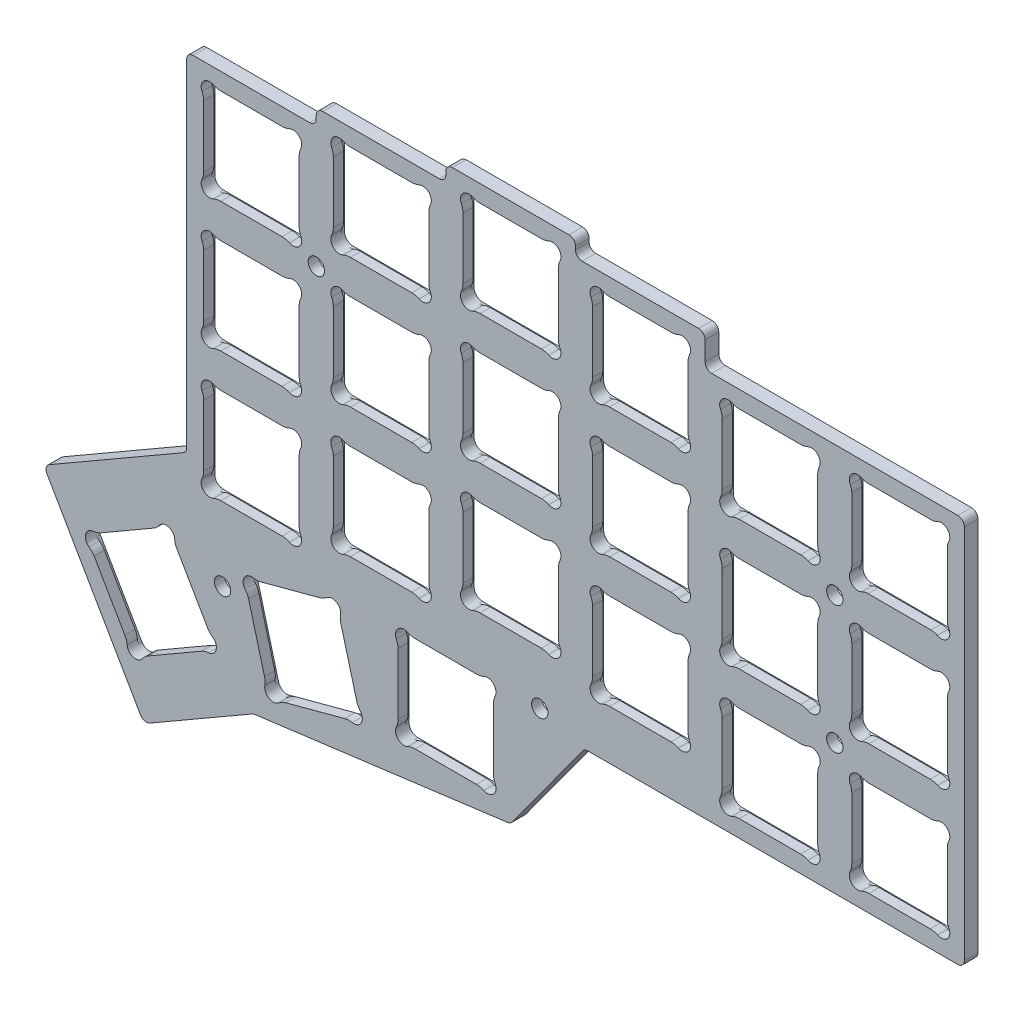
SolidWorks part; units mm, degrees
ref_plane "Front Plane" through (0, 0, 0) normal (0, 0, 1) x (1, 0, 0)
ref_plane "Top Plane" through (0, 0, 0) normal (0, 1, 0) x (1, 0, 0)
ref_plane "Right Plane" through (0, 0, 0) normal (1, 0, 0) x (0, 0, -1)
sketch "Model" plane through (0, 0, 0) normal (0, 0, 1) x (1, 0, 0)
  line L0 (-21.8431, 7.4481) -> (-8.6148, 30.3792)
  line L1 (-38.0636, 15.3297) -> (-23.771, 7.0696)
  line L2 (-75.3888, 20.2293) -> (-38.7189, 15.4592)
  line L3 (-86.2854, 34.8343) -> (-75.7419, 20.3766)
  line L4 (-29.1405, 92.9799) -> (-29.1405, 91.7303)
  line L5 (-8.8891, 91.2299) -> (-28.6402, 91.2299)
  line L6 (-8.3888, 90.7295) -> (-8.3888, 31.2555)
  line L7 (-86.6385, 34.9791) -> (-141.6396, 34.9791)
  line L8 (-142.1399, 90.7295) -> (-142.1399, 35.4795)
  line L9 (-104.6394, 91.2299) -> (-141.6396, 91.2299)
  line L10 (-104.139, 95.4793) -> (-104.139, 91.7303)
  line L11 (-85.6402, 95.9797) -> (-103.6387, 95.9797)
  line L12 (-85.1399, 97.7297) -> (-85.1399, 96.4801)
  line L13 (-67.6393, 98.2301) -> (-84.6395, 98.2301)
  line L14 (-67.1389, 96.4801) -> (-67.1389, 97.7297)
  line L15 (-48.6401, 95.9797) -> (-66.6385, 95.9797)
  line L16 (-48.1397, 93.9807) -> (-48.1397, 95.4793)
  line L17 (-29.6384, 93.4803) -> (-47.6393, 93.4803)
  line L18 (135.1563, 30.6526) -> (116.2359, 41.5721)
  line L19 (123.1828, 7.2669) -> (135.5373, 28.7222)
  line L20 (106.9623, 15.1485) -> (121.2549, 6.8884)
  line L21 (69.6371, 20.0481) -> (106.307, 15.278)
  line L22 (58.7405, 34.6531) -> (69.284, 20.1955)
  line L23 (115.8854, 92.7987) -> (115.8828, 42.2376)
  line L24 (58.3874, 34.7979) -> (3.3863, 34.7979)
  line L25 (2.886, 90.5483) -> (2.886, 35.2983)
  line L26 (40.3865, 91.0487) -> (3.3863, 91.0487)
  line L27 (40.8869, 95.2981) -> (40.8869, 91.5491)
  line L28 (59.3857, 95.7985) -> (41.3872, 95.7985)
  line L29 (59.886, 97.5485) -> (59.886, 96.2989)
  line L30 (77.3866, 98.0489) -> (60.3864, 98.0489)
  line L31 (77.887, 96.2989) -> (77.887, 97.5485)
  line L32 (96.3858, 95.7985) -> (78.3874, 95.7985)
  line L33 (96.8862, 93.7995) -> (96.8862, 95.2981)
  line L34 (115.3875, 93.2991) -> (97.3866, 93.2991)
  line L35 (20.1915, -96.2476) -> (6.9631, -73.3165)
  line L36 (36.4119, -88.366) -> (22.1193, -96.6261)
  line L37 (73.7371, -83.4663) -> (37.0672, -88.2365)
  line L38 (84.6337, -68.8614) -> (74.0902, -83.319)
  line L39 (27.4889, -10.7157) -> (27.4889, -11.9654)
  line L40 (7.2375, -12.4658) -> (26.9885, -12.4658)
  line L41 (6.7371, -12.9662) -> (6.7371, -72.4402)
  line L42 (84.9868, -68.7166) -> (139.9879, -68.7166)
  line L43 (140.4883, -12.9662) -> (140.4883, -68.2162)
  line L44 (102.9878, -12.4658) -> (139.9879, -12.4658)
  line L45 (102.4874, -8.2164) -> (102.4874, -11.9654)
  line L46 (83.9886, -7.716) -> (101.987, -7.716)
  line L47 (83.4882, -5.9659) -> (83.4882, -7.2156)
  line L48 (65.9876, -5.4656) -> (82.9878, -5.4656)
  line L49 (65.4872, -7.2156) -> (65.4872, -5.9659)
  line L50 (46.9884, -7.716) -> (64.9869, -7.716)
  line L51 (46.488, -9.715) -> (46.488, -8.2164)
  line L52 (27.9867, -10.2154) -> (45.9877, -10.2154)
  line L53 (-136.808, -73.043) -> (-117.8876, -62.1236)
  line L54 (-124.8344, -96.4288) -> (-137.189, -74.9734)
  line L55 (-108.614, -88.5472) -> (-122.9066, -96.8073)
  line L56 (-71.2888, -83.6475) -> (-107.9587, -88.4176)
  line L57 (-60.3922, -69.0425) -> (-70.9357, -83.5002)
  line L58 (-117.537, -10.8969) -> (-117.5345, -61.4581)
  line L59 (-60.0391, -68.8978) -> (-5.038, -68.8978)
  line L60 (-4.5376, -13.1474) -> (-4.5376, -68.3974)
  line L61 (-42.0381, -12.647) -> (-5.038, -12.647)
  line L62 (-42.5385, -8.3976) -> (-42.5385, -12.1466)
  line L63 (-61.0373, -7.8972) -> (-43.0389, -7.8972)
  line L64 (-61.5377, -6.1471) -> (-61.5377, -7.3968)
  line L65 (-79.0383, -5.6467) -> (-62.0381, -5.6467)
  line L66 (-79.5387, -7.3968) -> (-79.5387, -6.1471)
  line L67 (-98.0375, -7.8972) -> (-80.039, -7.8972)
  line L68 (-98.5378, -9.8962) -> (-98.5378, -8.3976)
  line L69 (-117.0392, -10.3965) -> (-99.0382, -10.3965)
  line L70 (138.9148, 92.1117) -> (138.9148, 33.3582)
  line L71 (138.1649, 32.9251) -> (119.446, 43.7282)
  line L72 (119.196, 44.1613) -> (119.196, 92.1092)
  line L73 (119.6959, 92.6092) -> (138.4148, 92.6117)
  line L74 (-140.5665, -11.584) -> (-140.5665, -70.3375)
  line L75 (-139.8166, -70.7706) -> (-121.0977, -59.9674)
  line L76 (-120.8476, -59.5344) -> (-120.8476, -11.5865)
  line L77 (-121.3476, -11.0865) -> (-140.0664, -11.084)
  line L78 (18.8966, 74.9256) -> (4.8966, 74.9256)
  line L79 (4.8966, 74.9256) -> (4.8966, 88.9256)
  line L80 (4.8966, 88.9256) -> (18.8966, 88.9256)
  line L81 (18.8966, 88.9256) -> (18.8966, 74.9256)
  line L82 (18.8966, 55.9256) -> (4.8966, 55.9256)
  line L83 (4.8966, 55.9256) -> (4.8966, 69.9256)
  line L84 (4.8966, 69.9256) -> (18.8966, 69.9256)
  line L85 (18.8966, 69.9256) -> (18.8966, 55.9256)
  line L86 (18.8966, 36.9256) -> (4.8966, 36.9256)
  line L87 (4.8966, 36.9256) -> (4.8966, 50.9256)
  line L88 (4.8966, 50.9256) -> (18.8966, 50.9256)
  line L89 (18.8966, 50.9256) -> (18.8966, 36.9256)
  line L90 (37.8948, 74.9262) -> (23.8948, 74.9262)
  line L91 (23.8948, 74.9262) -> (23.8948, 88.9262)
  line L92 (23.8948, 88.9262) -> (37.8948, 88.9262)
  line L93 (37.8948, 88.9262) -> (37.8948, 74.9262)
  line L94 (37.8948, 55.9262) -> (23.8948, 55.9262)
  line L95 (23.8948, 55.9262) -> (23.8948, 69.9262)
  line L96 (23.8948, 69.9262) -> (37.8948, 69.9262)
  line L97 (37.8948, 69.9262) -> (37.8948, 55.9262)
  line L98 (37.8948, 36.9262) -> (23.8948, 36.9262)
  line L99 (23.8948, 36.9262) -> (23.8948, 50.9262)
  line L100 (23.8948, 50.9262) -> (37.8948, 50.9262)
  line L101 (37.8948, 50.9262) -> (37.8948, 36.9262)
  line L102 (56.895, 79.671) -> (42.895, 79.671)
  line L103 (42.895, 79.671) -> (42.895, 93.671)
  line L104 (42.895, 93.671) -> (56.895, 93.671)
  line L105 (56.895, 93.671) -> (56.895, 79.671)
  line L106 (56.895, 60.6711) -> (42.895, 60.6711)
  line L107 (42.895, 60.6711) -> (42.895, 74.6711)
  line L108 (42.895, 74.6711) -> (56.895, 74.6711)
  line L109 (56.895, 74.6711) -> (56.895, 60.6711)
  line L110 (56.895, 41.6711) -> (42.895, 41.6711)
  line L111 (42.895, 41.6711) -> (42.895, 55.6711)
  line L112 (42.895, 55.6711) -> (56.895, 55.6711)
  line L113 (56.895, 55.6711) -> (56.895, 41.6711)
  line L114 (75.897, 82.0499) -> (61.897, 82.0499)
  line L115 (61.897, 82.0499) -> (61.897, 96.0499)
  line L116 (61.897, 96.0499) -> (75.897, 96.0499)
  line L117 (75.897, 96.0499) -> (75.897, 82.0499)
  line L118 (75.897, 63.0499) -> (61.897, 63.0499)
  line L119 (61.897, 63.0499) -> (61.897, 77.0499)
  line L120 (61.897, 77.0499) -> (75.897, 77.0499)
  line L121 (75.897, 77.0499) -> (75.897, 63.0499)
  line L122 (75.897, 44.0499) -> (61.897, 44.0499)
  line L123 (61.897, 44.0499) -> (61.897, 58.0499)
  line L124 (61.897, 58.0499) -> (75.897, 58.0499)
  line L125 (75.897, 58.0499) -> (75.897, 44.0499)
  line L126 (94.8982, 79.6753) -> (80.8982, 79.6753)
  line L127 (80.8982, 79.6753) -> (80.8982, 93.6753)
  line L128 (80.8982, 93.6753) -> (94.8982, 93.6753)
  line L129 (94.8982, 93.6753) -> (94.8982, 79.6753)
  line L130 (94.8982, 60.6753) -> (80.8982, 60.6753)
  line L131 (80.8982, 60.6753) -> (80.8982, 74.6753)
  line L132 (80.8982, 74.6753) -> (94.8982, 74.6753)
  line L133 (94.8982, 74.6753) -> (94.8982, 60.6753)
  line L134 (94.8982, 41.6753) -> (80.8982, 41.6753)
  line L135 (80.8982, 41.6753) -> (80.8982, 55.6753)
  line L136 (80.8982, 55.6753) -> (94.8982, 55.6753)
  line L137 (94.8982, 55.6753) -> (94.8982, 41.6753)
  line L138 (113.9, 77.2905) -> (99.9, 77.2905)
  line L139 (99.9, 77.2905) -> (99.9, 91.2905)
  line L140 (99.9, 91.2905) -> (113.9, 91.2905)
  line L141 (113.9, 91.2905) -> (113.9, 77.2905)
  line L142 (113.9, 58.2905) -> (99.9, 58.2905)
  line L143 (99.9, 58.2905) -> (99.9, 72.2905)
  line L144 (99.9, 72.2905) -> (113.9, 72.2905)
  line L145 (113.9, 72.2905) -> (113.9, 58.2905)
  line L146 (113.9, 39.2905) -> (99.9, 39.2905)
  line L147 (99.9, 39.2905) -> (99.9, 53.2905)
  line L148 (99.9, 53.2905) -> (113.9, 53.2905)
  line L149 (113.9, 53.2905) -> (113.9, 39.2905)
  line L150 (85.4166, 22.0174) -> (71.4166, 22.0174)
  line L151 (71.4166, 22.0174) -> (71.4166, 36.0174)
  line L152 (71.4166, 36.0174) -> (85.4166, 36.0174)
  line L153 (85.4166, 36.0174) -> (85.4166, 22.0174)
  line L154 (104.3289, 17.734) -> (90.806, 21.3575)
  line L155 (90.806, 21.3575) -> (94.4294, 34.8805)
  line L156 (94.4294, 34.8805) -> (107.9524, 31.257)
  line L157 (107.9524, 31.257) -> (104.3289, 17.734)
  line L158 (124.1994, 13.0049) -> (112.075, 20.0049)
  line L159 (112.075, 20.0049) -> (119.075, 32.1293)
  line L160 (119.075, 32.1293) -> (131.1994, 25.1293)
  line L161 (131.1994, 25.1293) -> (124.1994, 13.0049)
  line L162 (-20.5483, -28.7701) -> (-6.5483, -28.7701)
  line L163 (-6.5483, -28.7701) -> (-6.5483, -14.7701)
  line L164 (-6.5483, -14.7701) -> (-20.5483, -14.7701)
  line L165 (-20.5483, -14.7701) -> (-20.5483, -28.7701)
  line L166 (-20.5483, -47.7701) -> (-6.5483, -47.7701)
  line L167 (-6.5483, -47.7701) -> (-6.5483, -33.7701)
  line L168 (-6.5483, -33.7701) -> (-20.5483, -33.7701)
  line L169 (-20.5483, -33.7701) -> (-20.5483, -47.7701)
  line L170 (-20.5483, -66.7701) -> (-6.5483, -66.7701)
  line L171 (-6.5483, -66.7701) -> (-6.5483, -52.7701)
  line L172 (-6.5483, -52.7701) -> (-20.5483, -52.7701)
  line L173 (-20.5483, -52.7701) -> (-20.5483, -66.7701)
  line L174 (-39.5464, -28.7694) -> (-25.5464, -28.7694)
  line L175 (-25.5464, -28.7694) -> (-25.5464, -14.7694)
  line L176 (-25.5464, -14.7694) -> (-39.5464, -14.7694)
  line L177 (-39.5464, -14.7694) -> (-39.5464, -28.7694)
  line L178 (-39.5464, -47.7694) -> (-25.5464, -47.7694)
  line L179 (-25.5464, -47.7694) -> (-25.5464, -33.7694)
  line L180 (-25.5464, -33.7694) -> (-39.5464, -33.7694)
  line L181 (-39.5464, -33.7694) -> (-39.5464, -47.7694)
  line L182 (-39.5464, -66.7694) -> (-25.5464, -66.7694)
  line L183 (-25.5464, -66.7694) -> (-25.5464, -52.7694)
  line L184 (-25.5464, -52.7694) -> (-39.5464, -52.7694)
  line L185 (-39.5464, -52.7694) -> (-39.5464, -66.7694)
  line L186 (-58.5467, -24.0246) -> (-44.5467, -24.0246)
  line L187 (-44.5467, -24.0246) -> (-44.5467, -10.0246)
  line L188 (-44.5467, -10.0246) -> (-58.5467, -10.0246)
  line L189 (-58.5467, -10.0246) -> (-58.5467, -24.0246)
  line L190 (-58.5467, -43.0246) -> (-44.5467, -43.0246)
  line L191 (-44.5467, -43.0246) -> (-44.5467, -29.0246)
  line L192 (-44.5467, -29.0246) -> (-58.5467, -29.0246)
  line L193 (-58.5467, -29.0246) -> (-58.5467, -43.0246)
  line L194 (-58.5467, -62.0246) -> (-44.5467, -62.0246)
  line L195 (-44.5467, -62.0246) -> (-44.5467, -48.0246)
  line L196 (-44.5467, -48.0246) -> (-58.5467, -48.0246)
  line L197 (-58.5467, -48.0246) -> (-58.5467, -62.0246)
  line L198 (-77.5486, -21.6458) -> (-63.5486, -21.6458)
  line L199 (-63.5486, -21.6458) -> (-63.5486, -7.6458)
  line L200 (-63.5486, -7.6458) -> (-77.5486, -7.6458)
  line L201 (-77.5486, -7.6458) -> (-77.5486, -21.6458)
  line L202 (-77.5486, -40.6458) -> (-63.5486, -40.6458)
  line L203 (-63.5486, -40.6458) -> (-63.5486, -26.6458)
  line L204 (-63.5486, -26.6458) -> (-77.5486, -26.6458)
  line L205 (-77.5486, -26.6458) -> (-77.5486, -40.6458)
  line L206 (-77.5486, -59.6458) -> (-63.5486, -59.6458)
  line L207 (-63.5486, -59.6458) -> (-63.5486, -45.6458)
  line L208 (-63.5486, -45.6458) -> (-77.5486, -45.6458)
  line L209 (-77.5486, -45.6458) -> (-77.5486, -59.6458)
  line L210 (-96.5499, -24.0204) -> (-82.5499, -24.0204)
  line L211 (-82.5499, -24.0204) -> (-82.5499, -10.0204)
  line L212 (-82.5499, -10.0204) -> (-96.5499, -10.0204)
  line L213 (-96.5499, -10.0204) -> (-96.5499, -24.0204)
  line L214 (-96.5499, -43.0203) -> (-82.5499, -43.0203)
  line L215 (-82.5499, -43.0203) -> (-82.5499, -29.0203)
  line L216 (-82.5499, -29.0203) -> (-96.5499, -29.0203)
  line L217 (-96.5499, -29.0203) -> (-96.5499, -43.0203)
  line L218 (-96.5499, -62.0203) -> (-82.5499, -62.0203)
  line L219 (-82.5499, -62.0203) -> (-82.5499, -48.0203)
  line L220 (-82.5499, -48.0203) -> (-96.5499, -48.0203)
  line L221 (-96.5499, -48.0203) -> (-96.5499, -62.0203)
  line L222 (-115.5516, -26.4052) -> (-101.5516, -26.4052)
  line L223 (-101.5516, -26.4052) -> (-101.5516, -12.4052)
  line L224 (-101.5516, -12.4052) -> (-115.5516, -12.4052)
  line L225 (-115.5516, -12.4052) -> (-115.5516, -26.4052)
  line L226 (-115.5516, -45.4052) -> (-101.5516, -45.4052)
  line L227 (-101.5516, -45.4052) -> (-101.5516, -31.4052)
  line L228 (-101.5516, -31.4052) -> (-115.5516, -31.4052)
  line L229 (-115.5516, -31.4052) -> (-115.5516, -45.4052)
  line L230 (-115.5516, -64.4052) -> (-101.5516, -64.4052)
  line L231 (-101.5516, -64.4052) -> (-101.5516, -50.4052)
  line L232 (-101.5516, -50.4052) -> (-115.5516, -50.4052)
  line L233 (-115.5516, -50.4052) -> (-115.5516, -64.4052)
  line L234 (-87.0683, -81.6783) -> (-73.0683, -81.6783)
  line L235 (-73.0683, -81.6783) -> (-73.0683, -67.6783)
  line L236 (-73.0683, -67.6783) -> (-87.0683, -67.6783)
  line L237 (-87.0683, -67.6783) -> (-87.0683, -81.6783)
  line L238 (-105.9806, -85.9616) -> (-92.4576, -82.3382)
  line L239 (-92.4576, -82.3382) -> (-96.0811, -68.8152)
  line L240 (-96.0811, -68.8152) -> (-109.6041, -72.4387)
  line L241 (-109.6041, -72.4387) -> (-105.9806, -85.9616)
  line L242 (-125.851, -90.6908) -> (-113.7267, -83.6908)
  line L243 (-113.7267, -83.6908) -> (-120.7267, -71.5664)
  line L244 (-120.7267, -71.5664) -> (-132.851, -78.5664)
  line L245 (-132.851, -78.5664) -> (-125.851, -90.6908)
  spline S0 degree 3 poles (-8.6153, 30.3807) (-8.4626, 30.6458) (-8.3842, 30.9472) (-8.3882, 31.2532) knots 0 0 0 0 1 1 1 1
  spline S1 degree 3 poles (-21.8439, 7.4422) (-21.8429, 7.4437) (-21.8419, 7.4453) (-21.8408, 7.4468) knots 1 1 1 1 2 2 2 2
  spline S2 degree 3 poles (-23.769, 7.0673) (-23.1339, 6.6392) (-22.272, 6.8071) (-21.8439, 7.4422) knots 0 0 0 0 1 1 1 1
  spline S3 degree 3 poles (-38.063, 15.3284) (-38.2765, 15.3928) (-38.4957, 15.4362) (-38.7176, 15.4579) knots 0 0 0 0 1 1 1 1
  spline S4 degree 3 poles (-75.7416, 20.3746) (-75.6478, 20.2809) (-75.5206, 20.2283) (-75.3881, 20.2283) knots 0 0 0 0 1 1 1 1
  spline S5 degree 3 poles (-29.1383, 92.9782) (-29.1382, 93.2543) (-29.362, 93.4782) (-29.6381, 93.4783) knots 0 0 0 0 1 1 1 1
  spline S6 degree 3 poles (-29.1383, 91.7282) (-29.1383, 91.4521) (-28.9145, 91.2282) (-28.6384, 91.2281) (-28.6383, 91.2281) (-28.6382, 91.2281) (-28.6381, 91.2281) knots 0 0 0 0 1 1 1 2 2 2 2
  spline S7 degree 3 poles (-86.2846, 34.8318) (-86.3784, 34.9256) (-86.5056, 34.9783) (-86.6385, 34.9791) knots 0 0 0 0 1 1 1 1
  spline S8 degree 3 poles (-142.1382, 35.4782) (-142.1381, 35.2021) (-141.9142, 34.9783) (-141.6381, 34.9783) knots 0 0 0 0 1 1 1 1
  spline S9 degree 3 poles (-141.638, 91.2281) (-141.9142, 91.2282) (-142.1381, 91.0044) (-142.1382, 90.7282) knots 0 0 0 0 1 1 1 1
  spline S10 degree 3 poles (-104.6382, 91.2281) (-104.362, 91.228) (-104.1381, 91.4518) (-104.138, 91.728) (-104.138, 91.7281) (-104.138, 91.7281) (-104.138, 91.7282) knots 0 0 0 0 1 1 1 2 2 2 2
  spline S11 degree 3 poles (-103.6382, 95.9781) (-103.9142, 95.9781) (-104.138, 95.7543) (-104.138, 95.4783) knots 0 0 0 0 1 1 1 1
  spline S12 degree 3 poles (-85.6382, 95.9781) (-85.3621, 95.9781) (-85.1382, 96.2019) (-85.1381, 96.478) (-85.1381, 96.4781) (-85.1381, 96.4782) (-85.1381, 96.4783) knots 0 0 0 0 1 1 1 2 2 2 2
  spline S13 degree 3 poles (-84.6382, 98.2283) (-84.9144, 98.2283) (-85.1382, 98.0044) (-85.1381, 97.7282) knots 0 0 0 0 1 1 1 1
  spline S14 degree 3 poles (-67.1381, 97.7282) (-67.1381, 98.0043) (-67.3619, 98.2283) (-67.638, 98.2283) knots 0 0 0 0 2 2 2 2
  spline S15 degree 3 poles (-67.1381, 96.4783) (-67.1382, 96.2021) (-66.9144, 95.9782) (-66.6383, 95.9781) (-66.6382, 95.9781) (-66.6381, 95.9781) (-66.638, 95.9781) knots 0 0 0 0 1 1 1 2 2 2 2
  spline S16 degree 3 poles (-48.1382, 95.4783) (-48.1383, 95.7543) (-48.362, 95.9781) (-48.6381, 95.9781) knots 0 0 0 0 1 1 1 1
  spline S17 degree 3 poles (-48.1382, 93.9782) (-48.1381, 93.702) (-47.9142, 93.4782) (-47.6381, 93.4783) knots 0 0 0 0 1 1 1 1
  spline S18 degree 3 poles (-8.3882, 90.7282) (-8.3883, 91.0043) (-8.6121, 91.228) (-8.8881, 91.2281) knots 0 0 0 0 1 1 1 1
  spline S19 degree 3 poles (115.8851, 42.2368) (115.8929, 41.9725) (116.0232, 41.7268) (116.2377, 41.5721) knots 0 0 0 0 1 1 1 1
  spline S20 degree 3 poles (135.163, 30.647) (135.1614, 30.648) (135.1599, 30.6491) (135.1583, 30.6501) knots 1 1 1 1 2 2 2 2
  spline S21 degree 3 poles (135.5373, 28.7222) (135.9659, 29.3571) (135.7981, 30.2189) (135.163, 30.647) knots 0 0 0 0 1 1 1 1
  spline S22 degree 3 poles (123.182, 7.261) (123.183, 7.2625) (123.184, 7.2641) (123.1851, 7.2656) knots 1 1 1 1 2 2 2 2
  spline S23 degree 3 poles (121.2569, 6.8861) (121.892, 6.4581) (122.7539, 6.6259) (123.182, 7.261) knots 0 0 0 0 1 1 1 1
  spline S24 degree 3 poles (106.9629, 15.1472) (106.7494, 15.2117) (106.5302, 15.255) (106.3083, 15.2768) knots 0 0 0 0 1 1 1 1
  spline S25 degree 3 poles (69.2843, 20.1934) (69.3781, 20.0997) (69.5053, 20.0471) (69.6378, 20.0471) knots 0 0 0 0 1 1 1 1
  spline S26 degree 3 poles (115.8876, 92.797) (115.8877, 93.0731) (115.6639, 93.297) (115.3878, 93.2971) knots 0 0 0 0 1 1 1 1
  spline S27 degree 3 poles (58.7413, 34.6506) (58.6475, 34.7444) (58.5203, 34.7971) (58.3874, 34.7979) knots 0 0 0 0 1 1 1 1
  spline S28 degree 3 poles (2.8877, 35.297) (2.8878, 35.0209) (3.1117, 34.7971) (3.3878, 34.7971) knots 0 0 0 0 1 1 1 1
  spline S29 degree 3 poles (3.3879, 91.0469) (3.1117, 91.047) (2.8878, 90.8232) (2.8877, 90.547) knots 0 0 0 0 1 1 1 1
  spline S30 degree 3 poles (40.3877, 91.0469) (40.6639, 91.0468) (40.8878, 91.2706) (40.8879, 91.5468) (40.8879, 91.5469) (40.8879, 91.5469) (40.8879, 91.547) knots 0 0 0 0 1 1 1 2 2 2 2
  spline S31 degree 3 poles (41.3877, 95.797) (41.1117, 95.7969) (40.8879, 95.5731) (40.8879, 95.2971) knots 0 0 0 0 1 1 1 1
  spline S32 degree 3 poles (59.3877, 95.797) (59.6638, 95.7969) (59.8877, 96.0207) (59.8878, 96.2968) (59.8878, 96.2969) (59.8878, 96.297) (59.8878, 96.2971) knots 0 0 0 0 1 1 1 2 2 2 2
  spline S33 degree 3 poles (60.3877, 98.0471) (60.1115, 98.0471) (59.8877, 97.8232) (59.8878, 97.547) knots 0 0 0 0 1 1 1 1
  spline S34 degree 3 poles (77.8878, 97.547) (77.8878, 97.8232) (77.664, 98.0471) (77.3879, 98.0471) knots 0 0 0 0 2 2 2 2
  spline S35 degree 3 poles (77.8878, 96.2971) (77.8877, 96.0209) (78.1115, 95.797) (78.3876, 95.797) (78.3877, 95.797) (78.3878, 95.797) (78.3879, 95.797) knots 0 0 0 0 1 1 1 2 2 2 2
  spline S36 degree 3 poles (96.8877, 95.2971) (96.8876, 95.5731) (96.6639, 95.7969) (96.3878, 95.797) knots 0 0 0 0 1 1 1 1
  spline S37 degree 3 poles (96.8877, 93.797) (96.8878, 93.5208) (97.1117, 93.297) (97.3878, 93.2971) knots 0 0 0 0 1 1 1 1
  spline S38 degree 3 poles (6.9637, -73.315) (6.8109, -73.0499) (6.7325, -72.7484) (6.7366, -72.4425) knots 0 0 0 0 1 1 1 1
  spline S39 degree 3 poles (20.1923, -96.2535) (20.1912, -96.252) (20.1902, -96.2504) (20.1892, -96.2489) knots 1 1 1 1 2 2 2 2
  spline S40 degree 3 poles (22.1173, -96.6284) (21.4822, -97.0564) (20.6203, -96.8886) (20.1923, -96.2535) knots 0 0 0 0 1 1 1 1
  spline S41 degree 3 poles (36.4114, -88.3673) (36.6248, -88.3028) (36.844, -88.2594) (37.0659, -88.2377) knots 0 0 0 0 1 1 1 1
  spline S42 degree 3 poles (74.0899, -83.3211) (73.9962, -83.4148) (73.869, -83.4674) (73.7364, -83.4674) knots 0 0 0 0 1 1 1 1
  spline S43 degree 3 poles (27.4866, -10.7175) (27.4865, -10.4414) (27.7103, -10.2175) (27.9865, -10.2174) knots 0 0 0 0 1 1 1 1
  spline S44 degree 3 poles (27.4866, -11.9674) (27.4866, -12.2436) (27.2628, -12.4675) (26.9867, -12.4676) (26.9866, -12.4676) (26.9865, -12.4676) (26.9865, -12.4676) knots 0 0 0 0 1 1 1 2 2 2 2
  spline S45 degree 3 poles (84.633, -68.8639) (84.7267, -68.7701) (84.8539, -68.7174) (84.9868, -68.7166) knots 0 0 0 0 1 1 1 1
  spline S46 degree 3 poles (140.4865, -68.2175) (140.4864, -68.4936) (140.2625, -68.7174) (139.9864, -68.7173) knots 0 0 0 0 1 1 1 1
  spline S47 degree 3 poles (139.9864, -12.4676) (140.2625, -12.4675) (140.4864, -12.6913) (140.4865, -12.9674) knots 0 0 0 0 1 1 1 1
  spline S48 degree 3 poles (102.9865, -12.4676) (102.7103, -12.4676) (102.4864, -12.2438) (102.4864, -11.9677) (102.4864, -11.9676) (102.4864, -11.9675) (102.4864, -11.9674) knots 0 0 0 0 1 1 1 2 2 2 2
  spline S49 degree 3 poles (101.9865, -7.7175) (102.2625, -7.7176) (102.4863, -7.9413) (102.4864, -8.2174) knots 0 0 0 0 1 1 1 1
  spline S50 degree 3 poles (83.9865, -7.7175) (83.7104, -7.7176) (83.4865, -7.4938) (83.4864, -7.2176) (83.4864, -7.2176) (83.4864, -7.2175) (83.4864, -7.2174) knots 0 0 0 0 1 1 1 2 2 2 2
  spline S51 degree 3 poles (82.9865, -5.4673) (83.2627, -5.4674) (83.4865, -5.6913) (83.4864, -5.9675) knots 0 0 0 0 1 1 1 1
  spline S52 degree 3 poles (65.4865, -5.9675) (65.4864, -5.6913) (65.7102, -5.4674) (65.9863, -5.4673) knots 0 0 0 0 2 2 2 2
  spline S53 degree 3 poles (65.4865, -7.2174) (65.4865, -7.4935) (65.2627, -7.7174) (64.9866, -7.7175) (64.9865, -7.7175) (64.9864, -7.7175) (64.9863, -7.7175) knots 0 0 0 0 1 1 1 2 2 2 2
  spline S54 degree 3 poles (46.4865, -8.2174) (46.4866, -7.9413) (46.7103, -7.7176) (46.9864, -7.7175) knots 0 0 0 0 1 1 1 1
  spline S55 degree 3 poles (46.4865, -9.7175) (46.4865, -9.9937) (46.2625, -10.2175) (45.9864, -10.2174) knots 0 0 0 0 1 1 1 1
  spline S56 degree 3 poles (6.7366, -12.9674) (6.7366, -12.6914) (6.9604, -12.4676) (7.2365, -12.4676) knots 0 0 0 0 1 1 1 1
  spline S57 degree 3 poles (-117.5368, -61.4589) (-117.5446, -61.7232) (-117.6748, -61.9689) (-117.8893, -62.1236) knots 0 0 0 0 1 1 1 1
  spline S58 degree 3 poles (-136.8146, -73.0487) (-136.8131, -73.0476) (-136.8116, -73.0466) (-136.81, -73.0456) knots 1 1 1 1 2 2 2 2
  spline S59 degree 3 poles (-137.189, -74.9734) (-137.6176, -74.3386) (-137.4497, -73.4767) (-136.8146, -73.0487) knots 0 0 0 0 1 1 1 1
  spline S60 degree 3 poles (-124.8336, -96.4347) (-124.8347, -96.4331) (-124.8357, -96.4316) (-124.8367, -96.4301) knots 1 1 1 1 2 2 2 2
  spline S61 degree 3 poles (-122.9086, -96.8095) (-123.5437, -97.2376) (-124.4056, -97.0698) (-124.8336, -96.4347) knots 0 0 0 0 1 1 1 1
  spline S62 degree 3 poles (-108.6145, -88.5485) (-108.4011, -88.484) (-108.1819, -88.4406) (-107.96, -88.4189) knots 0 0 0 0 1 1 1 1
  spline S63 degree 3 poles (-70.936, -83.5022) (-71.0297, -83.596) (-71.1569, -83.6486) (-71.2895, -83.6485) knots 0 0 0 0 1 1 1 1
  spline S64 degree 3 poles (-117.5393, -10.8987) (-117.5394, -10.6226) (-117.3156, -10.3987) (-117.0394, -10.3986) knots 0 0 0 0 1 1 1 1
  spline S65 degree 3 poles (-60.3929, -69.0451) (-60.2992, -68.9513) (-60.172, -68.8986) (-60.0391, -68.8978) knots 0 0 0 0 1 1 1 1
  spline S66 degree 3 poles (-4.5394, -68.3987) (-4.5395, -68.6748) (-4.7634, -68.8986) (-5.0395, -68.8985) knots 0 0 0 0 1 1 1 1
  spline S67 degree 3 poles (-5.0395, -12.6488) (-4.7634, -12.6487) (-4.5395, -12.8725) (-4.5394, -13.1486) knots 0 0 0 0 1 1 1 1
  spline S68 degree 3 poles (-42.0394, -12.6488) (-42.3156, -12.6488) (-42.5395, -12.425) (-42.5395, -12.1489) (-42.5395, -12.1488) (-42.5395, -12.1487) (-42.5395, -12.1486) knots 0 0 0 0 1 1 1 2 2 2 2
  spline S69 degree 3 poles (-43.0394, -7.8987) (-42.7634, -7.8988) (-42.5396, -8.1225) (-42.5395, -8.3986) knots 0 0 0 0 1 1 1 1
  spline S70 degree 3 poles (-61.0394, -7.8987) (-61.3155, -7.8988) (-61.5394, -7.675) (-61.5395, -7.3988) (-61.5395, -7.3988) (-61.5395, -7.3987) (-61.5395, -7.3986) knots 0 0 0 0 1 1 1 2 2 2 2
  spline S71 degree 3 poles (-62.0394, -5.6485) (-61.7632, -5.6486) (-61.5394, -5.8725) (-61.5395, -6.1486) knots 0 0 0 0 1 1 1 1
  spline S72 degree 3 poles (-79.5394, -6.1486) (-79.5395, -5.8725) (-79.3157, -5.6486) (-79.0396, -5.6485) knots 0 0 0 0 2 2 2 2
  spline S73 degree 3 poles (-79.5394, -7.3986) (-79.5394, -7.6747) (-79.7632, -7.8986) (-80.0393, -7.8987) (-80.0394, -7.8987) (-80.0395, -7.8987) (-80.0396, -7.8987) knots 0 0 0 0 1 1 1 2 2 2 2
  spline S74 degree 3 poles (-98.5394, -8.3986) (-98.5393, -8.1225) (-98.3156, -7.8988) (-98.0395, -7.8987) knots 0 0 0 0 1 1 1 1
  spline S75 degree 3 poles (-98.5394, -9.8987) (-98.5394, -10.1748) (-98.7634, -10.3986) (-99.0395, -10.3986) knots 0 0 0 0 1 1 1 1
  spline S76 degree 3 poles (-123.6381, 52.6314) (-124.2456, 52.6314) (-124.7381, 53.1239) (-124.7381, 53.7314) (-124.7381, 54.3389) (-124.2456, 54.8314) (-123.6381, 54.8314) knots 2 2 2 2 3 3 3 4 4 4 4
  spline S77 degree 3 poles (-123.6381, 54.8314) (-123.0306, 54.8314) (-122.5381, 54.3389) (-122.5381, 53.7314) (-122.5381, 53.1239) (-123.0306, 52.6314) (-123.6381, 52.6314) knots 0 0 0 0 1 1 1 2 2 2 2
  spline S78 degree 3 poles (-123.6381, 71.3814) (-124.2456, 71.3814) (-124.7381, 71.8739) (-124.7381, 72.4814) (-124.7381, 73.0889) (-124.2456, 73.5814) (-123.6381, 73.5814) knots 2 2 2 2 3 3 3 4 4 4 4
  spline S79 degree 3 poles (-123.6381, 73.5814) (-123.0306, 73.5814) (-122.5381, 73.0889) (-122.5381, 72.4814) (-122.5381, 71.8739) (-123.0306, 71.3814) (-123.6381, 71.3814) knots 0 0 0 0 1 1 1 2 2 2 2
  spline S80 degree 3 poles (-47.6381, 75.1312) (-48.2456, 75.1312) (-48.7381, 75.6237) (-48.7381, 76.2312) (-48.7381, 76.8387) (-48.2456, 77.3312) (-47.6381, 77.3312) knots 2 2 2 2 3 3 3 4 4 4 4
  spline S81 degree 3 poles (-47.6381, 77.3312) (-47.0306, 77.3312) (-46.5381, 76.8387) (-46.5381, 76.2312) (-46.5381, 75.6237) (-47.0306, 75.1312) (-47.6381, 75.1312) knots 0 0 0 0 1 1 1 2 2 2 2
  spline S82 degree 3 poles (-80.388, 35.3813) (-80.9956, 35.3813) (-81.488, 35.8738) (-81.488, 36.4813) (-81.488, 37.0888) (-80.9956, 37.5813) (-80.388, 37.5813) knots 2 2 2 2 3 3 3 4 4 4 4
  spline S83 degree 3 poles (-80.388, 37.5813) (-79.7805, 37.5813) (-79.288, 37.0888) (-79.288, 36.4813) (-79.288, 35.8738) (-79.7805, 35.3813) (-80.388, 35.3813) knots 0 0 0 0 1 1 1 2 2 2 2
  spline S84 degree 3 poles (-33.8881, 27.6312) (-34.4956, 27.6312) (-34.9881, 28.1237) (-34.9881, 28.7312) (-34.9881, 29.3388) (-34.4956, 29.8312) (-33.8881, 29.8312) knots 2 2 2 2 3 3 3 4 4 4 4
  spline S85 degree 3 poles (-33.8881, 29.8312) (-33.2805, 29.8312) (-32.7881, 29.3388) (-32.7881, 28.7312) (-32.7881, 28.1237) (-33.2805, 27.6312) (-33.8881, 27.6312) knots 0 0 0 0 1 1 1 2 2 2 2
  spline S86 degree 3 poles (21.3878, 52.4502) (20.7803, 52.4502) (20.2878, 52.9427) (20.2878, 53.5502) (20.2878, 54.1578) (20.7803, 54.6502) (21.3878, 54.6502) knots 2 2 2 2 3 3 3 4 4 4 4
  spline S87 degree 3 poles (21.3878, 54.6502) (21.9953, 54.6502) (22.4878, 54.1578) (22.4878, 53.5502) (22.4878, 52.9427) (21.9953, 52.4502) (21.3878, 52.4502) knots 0 0 0 0 1 1 1 2 2 2 2
  spline S88 degree 3 poles (97.3878, 74.95) (96.7803, 74.95) (96.2878, 75.4425) (96.2878, 76.05) (96.2878, 76.6575) (96.7803, 77.15) (97.3878, 77.15) knots 2 2 2 2 3 3 3 4 4 4 4
  spline S89 degree 3 poles (97.3878, 77.15) (97.9953, 77.15) (98.4878, 76.6575) (98.4878, 76.05) (98.4878, 75.4425) (97.9953, 74.95) (97.3878, 74.95) knots 0 0 0 0 1 1 1 2 2 2 2
  spline S90 degree 3 poles (64.6379, 35.2001) (64.0303, 35.2001) (63.5379, 35.6926) (63.5379, 36.3001) (63.5379, 36.9076) (64.0303, 37.4001) (64.6379, 37.4001) knots 2 2 2 2 3 3 3 4 4 4 4
  spline S91 degree 3 poles (64.6379, 37.4001) (65.2454, 37.4001) (65.7379, 36.9076) (65.7379, 36.3001) (65.7379, 35.6926) (65.2454, 35.2001) (64.6379, 35.2001) knots 0 0 0 0 1 1 1 2 2 2 2
  spline S92 degree 3 poles (111.1378, 27.4501) (110.5303, 27.4501) (110.0378, 27.9425) (110.0378, 28.5501) (110.0378, 29.1576) (110.5303, 29.65) (111.1378, 29.65) knots 2 2 2 2 3 3 3 4 4 4 4
  spline S93 degree 3 poles (111.1378, 29.65) (111.7454, 29.65) (112.2378, 29.1576) (112.2378, 28.5501) (112.2378, 27.9425) (111.7454, 27.4501) (111.1378, 27.4501) knots 0 0 0 0 1 1 1 2 2 2 2
  spline S94 degree 3 poles (121.9864, -51.0642) (122.5939, -51.0642) (123.0864, -50.5718) (123.0864, -49.9642) (123.0864, -49.3567) (122.5939, -48.8642) (121.9864, -48.8642) knots 2 2 2 2 3 3 3 4 4 4 4
  spline S95 degree 3 poles (121.9864, -48.8642) (121.3789, -48.8642) (120.8864, -49.3567) (120.8864, -49.9642) (120.8864, -50.5718) (121.3789, -51.0642) (121.9864, -51.0642) knots 0 0 0 0 1 1 1 2 2 2 2
  spline S96 degree 3 poles (121.9864, -32.3142) (122.5939, -32.3142) (123.0864, -31.8218) (123.0864, -31.2142) (123.0864, -30.6067) (122.5939, -30.1142) (121.9864, -30.1142) knots 2 2 2 2 3 3 3 4 4 4 4
  spline S97 degree 3 poles (121.9864, -30.1142) (121.3789, -30.1142) (120.8864, -30.6067) (120.8864, -31.2142) (120.8864, -31.8218) (121.3789, -32.3142) (121.9864, -32.3142) knots 0 0 0 0 1 1 1 2 2 2 2
  spline S98 degree 3 poles (45.9864, -28.5644) (46.5939, -28.5644) (47.0864, -28.072) (47.0864, -27.4644) (47.0864, -26.8569) (46.5939, -26.3644) (45.9864, -26.3644) knots 2 2 2 2 3 3 3 4 4 4 4
  spline S99 degree 3 poles (45.9864, -26.3644) (45.3789, -26.3644) (44.8864, -26.8569) (44.8864, -27.4644) (44.8864, -28.072) (45.3789, -28.5644) (45.9864, -28.5644) knots 0 0 0 0 1 1 1 2 2 2 2
  spline S100 degree 3 poles (78.7364, -68.3144) (79.3439, -68.3144) (79.8364, -67.8219) (79.8364, -67.2144) (79.8364, -66.6069) (79.3439, -66.1144) (78.7364, -66.1144) knots 2 2 2 2 3 3 3 4 4 4 4
  spline S101 degree 3 poles (78.7364, -66.1144) (78.1288, -66.1144) (77.6364, -66.6069) (77.6364, -67.2144) (77.6364, -67.8219) (78.1288, -68.3144) (78.7364, -68.3144) knots 0 0 0 0 1 1 1 2 2 2 2
  spline S102 degree 3 poles (32.2364, -76.0644) (32.8439, -76.0644) (33.3364, -75.5719) (33.3364, -74.9644) (33.3364, -74.3569) (32.8439, -73.8644) (32.2364, -73.8644) knots 2 2 2 2 3 3 3 4 4 4 4
  spline S103 degree 3 poles (32.2364, -73.8644) (31.6289, -73.8644) (31.1364, -74.3569) (31.1364, -74.9644) (31.1364, -75.5719) (31.6289, -76.0644) (32.2364, -76.0644) knots 0 0 0 0 1 1 1 2 2 2 2
  spline S104 degree 3 poles (-23.0395, -51.2454) (-22.432, -51.2454) (-21.9395, -50.7529) (-21.9395, -50.1454) (-21.9395, -49.5379) (-22.432, -49.0454) (-23.0395, -49.0454) knots 2 2 2 2 3 3 3 4 4 4 4
  spline S105 degree 3 poles (-23.0395, -49.0454) (-23.647, -49.0454) (-24.1395, -49.5379) (-24.1395, -50.1454) (-24.1395, -50.7529) (-23.647, -51.2454) (-23.0395, -51.2454) knots 0 0 0 0 1 1 1 2 2 2 2
  spline S106 degree 3 poles (-99.0395, -28.7456) (-98.432, -28.7456) (-97.9395, -28.2531) (-97.9395, -27.6456) (-97.9395, -27.0381) (-98.432, -26.5456) (-99.0395, -26.5456) knots 2 2 2 2 3 3 3 4 4 4 4
  spline S107 degree 3 poles (-99.0395, -26.5456) (-99.647, -26.5456) (-100.1395, -27.0381) (-100.1395, -27.6456) (-100.1395, -28.2531) (-99.647, -28.7456) (-99.0395, -28.7456) knots 0 0 0 0 1 1 1 2 2 2 2
  spline S108 degree 3 poles (-66.2895, -68.4956) (-65.682, -68.4956) (-65.1895, -68.0031) (-65.1895, -67.3956) (-65.1895, -66.7881) (-65.682, -66.2956) (-66.2895, -66.2956) knots 2 2 2 2 3 3 3 4 4 4 4
  spline S109 degree 3 poles (-66.2895, -66.2956) (-66.8971, -66.2956) (-67.3895, -66.7881) (-67.3895, -67.3956) (-67.3895, -68.0031) (-66.8971, -68.4956) (-66.2895, -68.4956) knots 0 0 0 0 1 1 1 2 2 2 2
  spline S110 degree 3 poles (-112.7895, -76.2456) (-112.182, -76.2456) (-111.6895, -75.7531) (-111.6895, -75.1456) (-111.6895, -74.5381) (-112.182, -74.0456) (-112.7895, -74.0456) knots 2 2 2 2 3 3 3 4 4 4 4
  spline S111 degree 3 poles (-112.7895, -74.0456) (-113.397, -74.0456) (-113.8895, -74.5381) (-113.8895, -75.1456) (-113.8895, -75.7531) (-113.397, -76.2456) (-112.7895, -76.2456) knots 0 0 0 0 1 1 1 2 2 2 2
  spline S112 degree 3 poles (138.9148, 33.3582) (138.9148, 32.9733) (138.4982, 32.7327) (138.1649, 32.9251) knots 1 1 1 1 2 2 2 2
  spline S113 degree 3 poles (119.446, 43.7282) (119.2913, 43.8175) (119.196, 43.9826) (119.196, 44.1613) knots 3 3 3 3 4 4 4 4
  spline S114 degree 3 poles (119.196, 92.1092) (119.196, 92.3853) (119.4198, 92.6092) (119.6959, 92.6092) knots 5 5 5 5 6 6 6 6
  spline S115 degree 3 poles (138.4148, 92.6117) (138.6909, 92.6117) (138.9148, 92.3879) (138.9148, 92.1117) knots 7 7 7 7 8 8 8 8
  spline S116 degree 3 poles (-140.5665, -70.3375) (-140.5665, -70.7224) (-140.1499, -70.9629) (-139.8166, -70.7706) knots 1 1 1 1 2 2 2 2
  spline S117 degree 3 poles (-121.0977, -59.9674) (-120.943, -59.8781) (-120.8476, -59.7131) (-120.8476, -59.5344) knots 3 3 3 3 4 4 4 4
  spline S118 degree 3 poles (-120.8476, -11.5865) (-120.8476, -11.3103) (-121.0715, -11.0865) (-121.3476, -11.0865) knots 5 5 5 5 6 6 6 6
  spline S119 degree 3 poles (-140.0664, -11.084) (-140.3426, -11.0839) (-140.5665, -11.3078) (-140.5665, -11.584) knots 7 7 7 7 8 8 8 8
  spline S120 degree 3 poles (120.7443, 45.1272) (120.7443, 45.7347) (121.2368, 46.2272) (121.8443, 46.2272) (122.4518, 46.2272) (122.9443, 45.7347) (122.9443, 45.1272) knots 2 2 2 2 3 3 3 4 4 4 4
  spline S121 degree 3 poles (122.9443, 45.1272) (122.9443, 44.5197) (122.4518, 44.0272) (121.8443, 44.0272) (121.2368, 44.0272) (120.7443, 44.5197) (120.7443, 45.1272) knots 0 0 0 0 1 1 1 2 2 2 2
  spline S122 degree 3 poles (135.1763, 36.6063) (135.1763, 37.2138) (135.6688, 37.7063) (136.2763, 37.7063) (136.8838, 37.7063) (137.3763, 37.2138) (137.3763, 36.6063) knots 2 2 2 2 3 3 3 4 4 4 4
  spline S123 degree 3 poles (137.3763, 36.6063) (137.3763, 35.9988) (136.8838, 35.5063) (136.2763, 35.5063) (135.6688, 35.5063) (135.1763, 35.9988) (135.1763, 36.6063) knots 0 0 0 0 1 1 1 2 2 2 2
  spline S124 degree 3 poles (20.2878, 72.3002) (20.2878, 72.9078) (20.7803, 73.4002) (21.3878, 73.4002) (21.9953, 73.4002) (22.4878, 72.9078) (22.4878, 72.3002) knots 2 2 2 2 3 3 3 4 4 4 4
  spline S125 degree 3 poles (22.4878, 72.3002) (22.4878, 71.6927) (21.9953, 71.2002) (21.3878, 71.2002) (20.7803, 71.2002) (20.2878, 71.6927) (20.2878, 72.3002) knots 0 0 0 0 1 1 1 2 2 2 2
  spline S126 degree 3 poles (-122.3959, -58.5684) (-122.3959, -57.9609) (-122.8884, -57.4684) (-123.4959, -57.4684) (-124.1035, -57.4684) (-124.5959, -57.9609) (-124.5959, -58.5684) knots 2 2 2 2 3 3 3 4 4 4 4
  spline S127 degree 3 poles (-124.5959, -58.5684) (-124.5959, -59.1759) (-124.1035, -59.6684) (-123.4959, -59.6684) (-122.8884, -59.6684) (-122.3959, -59.1759) (-122.3959, -58.5684) knots 0 0 0 0 1 1 1 2 2 2 2
  spline S128 degree 3 poles (-136.8279, -67.0894) (-136.8279, -66.4818) (-137.3204, -65.9894) (-137.9279, -65.9894) (-138.5355, -65.9894) (-139.0279, -66.4818) (-139.0279, -67.0894) knots 2 2 2 2 3 3 3 4 4 4 4
  spline S129 degree 3 poles (-139.0279, -67.0894) (-139.0279, -67.6969) (-138.5355, -68.1894) (-137.9279, -68.1894) (-137.3204, -68.1894) (-136.8279, -67.6969) (-136.8279, -67.0894) knots 0 0 0 0 1 1 1 2 2 2 2
  spline S130 degree 3 poles (-21.9395, -31.3954) (-21.9395, -30.7879) (-22.432, -30.2954) (-23.0395, -30.2954) (-23.647, -30.2954) (-24.1395, -30.7879) (-24.1395, -31.3954) knots 2 2 2 2 3 3 3 4 4 4 4
  spline S131 degree 3 poles (-24.1395, -31.3954) (-24.1395, -32.0029) (-23.647, -32.4954) (-23.0395, -32.4954) (-22.432, -32.4954) (-21.9395, -32.0029) (-21.9395, -31.3954) knots 0 0 0 0 1 1 1 2 2 2 2
sketch "Sketch2" plane through (0, 0, 0) normal (0, 0, 1) x (1, 0, 0)
  line L0 (18.8966, 74.9256) -> (4.8966, 74.9256) construction
  line L1 (18.8966, 88.9256) -> (18.8966, 74.9256) construction
  line L2 (4.8966, 88.9256) -> (18.8966, 88.9256) construction
  line L3 (4.8966, 74.9256) -> (4.8966, 88.9256) construction
  line L4 (16.5141, 74.9256) -> (7.279, 74.9256)
  line L5 (18.8966, 86.5431) -> (18.8966, 77.308)
  line L6 (7.279, 88.9256) -> (16.5141, 88.9256)
  line L7 (4.8966, 77.308) -> (4.8966, 86.5431)
  line L8 (115.8854, 92.7987) -> (115.8828, 42.2376) construction
  line L9 (135.1563, 30.6526) -> (116.2359, 41.5721) construction
  line L10 (123.1828, 7.2669) -> (135.5373, 28.7222) construction
  line L11 (106.9623, 15.1485) -> (121.2549, 6.8884) construction
  line L12 (69.6371, 20.0481) -> (106.307, 15.278) construction
  line L13 (58.7405, 34.6531) -> (69.284, 20.1955) construction
  line L14 (85.4166, 36.0174) -> (85.4166, 22.0174) construction
  line L15 (85.4166, 22.0174) -> (71.4166, 22.0174) construction
  line L16 (71.4166, 22.0174) -> (71.4166, 36.0174) construction
  line L17 (71.4166, 36.0174) -> (85.4166, 36.0174) construction
  line L18 (107.9524, 31.257) -> (104.3289, 17.734) construction
  line L19 (104.3289, 17.734) -> (90.806, 21.3575) construction
  line L20 (90.806, 21.3575) -> (94.4294, 34.8805) construction
  line L21 (94.4294, 34.8805) -> (107.9524, 31.257) construction
  line L22 (112.075, 20.0049) -> (119.075, 32.1293) construction
  line L23 (119.075, 32.1293) -> (131.1994, 25.1293) construction
  line L24 (131.1994, 25.1293) -> (124.1994, 13.0049) construction
  line L25 (124.1994, 13.0049) -> (112.075, 20.0049) construction
  line L26 (99.9, 39.2905) -> (99.9, 53.2905) construction
  line L27 (99.9, 53.2905) -> (113.9, 53.2905) construction
  line L28 (113.9, 53.2905) -> (113.9, 39.2905) construction
  line L29 (113.9, 39.2905) -> (99.9, 39.2905) construction
  line L30 (80.8982, 41.6753) -> (80.8982, 55.6753) construction
  line L31 (80.8982, 55.6753) -> (94.8982, 55.6753) construction
  line L32 (94.8982, 55.6753) -> (94.8982, 41.6753) construction
  line L33 (94.8982, 41.6753) -> (80.8982, 41.6753) construction
  line L34 (58.3874, 34.7979) -> (3.3863, 34.7979) construction
  line L35 (61.897, 44.0499) -> (61.897, 58.0499) construction
  line L36 (61.897, 58.0499) -> (75.897, 58.0499) construction
  line L37 (75.897, 58.0499) -> (75.897, 44.0499) construction
  line L38 (75.897, 44.0499) -> (61.897, 44.0499) construction
  line L39 (42.895, 41.6711) -> (42.895, 55.6711) construction
  line L40 (42.895, 55.6711) -> (56.895, 55.6711) construction
  line L41 (56.895, 55.6711) -> (56.895, 41.6711) construction
  line L42 (56.895, 41.6711) -> (42.895, 41.6711) construction
  line L43 (23.8948, 36.9262) -> (23.8948, 50.9262) construction
  line L44 (23.8948, 50.9262) -> (37.8948, 50.9262) construction
  line L45 (37.8948, 50.9262) -> (37.8948, 36.9262) construction
  line L46 (37.8948, 36.9262) -> (23.8948, 36.9262) construction
  line L47 (18.8966, 50.9256) -> (18.8966, 36.9256) construction
  line L48 (18.8966, 36.9256) -> (4.8966, 36.9256) construction
  line L49 (4.8966, 36.9256) -> (4.8966, 50.9256) construction
  line L50 (4.8966, 50.9256) -> (18.8966, 50.9256) construction
  line L51 (99.9, 58.2905) -> (99.9, 72.2905) construction
  line L52 (99.9, 72.2905) -> (113.9, 72.2905) construction
  line L53 (113.9, 72.2905) -> (113.9, 58.2905) construction
  line L54 (113.9, 58.2905) -> (99.9, 58.2905) construction
  line L55 (94.8982, 74.6753) -> (94.8982, 60.6753) construction
  line L56 (94.8982, 60.6753) -> (80.8982, 60.6753) construction
  line L57 (80.8982, 60.6753) -> (80.8982, 74.6753) construction
  line L58 (80.8982, 74.6753) -> (94.8982, 74.6753) construction
  line L59 (61.897, 63.0499) -> (61.897, 77.0499) construction
  line L60 (61.897, 77.0499) -> (75.897, 77.0499) construction
  line L61 (75.897, 77.0499) -> (75.897, 63.0499) construction
  line L62 (75.897, 63.0499) -> (61.897, 63.0499) construction
  line L63 (42.895, 60.6711) -> (42.895, 74.6711) construction
  line L64 (42.895, 74.6711) -> (56.895, 74.6711) construction
  line L65 (56.895, 74.6711) -> (56.895, 60.6711) construction
  line L66 (56.895, 60.6711) -> (42.895, 60.6711) construction
  line L67 (23.8948, 55.9262) -> (23.8948, 69.9262) construction
  line L68 (23.8948, 69.9262) -> (37.8948, 69.9262) construction
  line L69 (37.8948, 69.9262) -> (37.8948, 55.9262) construction
  line L70 (37.8948, 55.9262) -> (23.8948, 55.9262) construction
  line L71 (4.8966, 55.9256) -> (4.8966, 69.9256) construction
  line L72 (4.8966, 69.9256) -> (18.8966, 69.9256) construction
  line L73 (18.8966, 69.9256) -> (18.8966, 55.9256) construction
  line L74 (18.8966, 55.9256) -> (4.8966, 55.9256) construction
  line L75 (99.9, 77.2905) -> (99.9, 91.2905) construction
  line L76 (99.9, 91.2905) -> (113.9, 91.2905) construction
  line L77 (113.9, 91.2905) -> (113.9, 77.2905) construction
  line L78 (113.9, 77.2905) -> (99.9, 77.2905) construction
  line L79 (80.8982, 79.6753) -> (80.8982, 93.6753) construction
  line L80 (80.8982, 93.6753) -> (94.8982, 93.6753) construction
  line L81 (94.8982, 93.6753) -> (94.8982, 79.6753) construction
  line L82 (94.8982, 79.6753) -> (80.8982, 79.6753) construction
  line L83 (61.897, 82.0499) -> (61.897, 96.0499) construction
  line L84 (61.897, 96.0499) -> (75.897, 96.0499) construction
  line L85 (75.897, 96.0499) -> (75.897, 82.0499) construction
  line L86 (75.897, 82.0499) -> (61.897, 82.0499) construction
  line L87 (2.886, 90.5483) -> (2.886, 35.2983) construction
  line L88 (42.895, 79.671) -> (42.895, 93.671) construction
  line L89 (42.895, 93.671) -> (56.895, 93.671) construction
  line L90 (56.895, 93.671) -> (56.895, 79.671) construction
  line L91 (56.895, 79.671) -> (42.895, 79.671) construction
  line L92 (23.8948, 88.9262) -> (37.8948, 88.9262) construction
  line L93 (37.8948, 88.9262) -> (37.8948, 74.9262) construction
  line L94 (37.8948, 74.9262) -> (23.8948, 74.9262) construction
  line L95 (23.8948, 74.9262) -> (23.8948, 88.9262) construction
  line L96 (115.8854, 92.7987) -> (115.8828, 42.2376) construction
  line L97 (135.1563, 30.6526) -> (116.2359, 41.5721) construction
  line L98 (123.1828, 7.2669) -> (135.5373, 28.7222) construction
  line L99 (106.9623, 15.1485) -> (121.2549, 6.8884) construction
  line L100 (69.6371, 20.0481) -> (106.307, 15.278) construction
  line L101 (58.7405, 34.6531) -> (69.284, 20.1955) construction
  line L102 (85.4166, 36.0174) -> (85.4166, 22.0174)
  line L103 (85.4166, 22.0174) -> (71.4166, 22.0174)
  line L104 (71.4166, 22.0174) -> (71.4166, 36.0174)
  line L105 (71.4166, 36.0174) -> (85.4166, 36.0174)
  line L106 (107.9524, 31.257) -> (104.3289, 17.734)
  line L107 (104.3289, 17.734) -> (90.806, 21.3575)
  line L108 (90.806, 21.3575) -> (94.4294, 34.8805)
  line L109 (94.4294, 34.8805) -> (107.9524, 31.257)
  line L110 (112.075, 20.0049) -> (119.075, 32.1293)
  line L111 (119.075, 32.1293) -> (131.1994, 25.1293)
  line L112 (131.1994, 25.1293) -> (124.1994, 13.0049)
  line L113 (124.1994, 13.0049) -> (112.075, 20.0049)
  line L114 (99.9, 39.2905) -> (99.9, 53.2905)
  line L115 (99.9, 53.2905) -> (113.9, 53.2905)
  line L116 (113.9, 53.2905) -> (113.9, 39.2905)
  line L117 (113.9, 39.2905) -> (99.9, 39.2905)
  line L118 (80.8982, 41.6753) -> (80.8982, 55.6753)
  line L119 (80.8982, 55.6753) -> (94.8982, 55.6753)
  line L120 (94.8982, 55.6753) -> (94.8982, 41.6753)
  line L121 (94.8982, 41.6753) -> (80.8982, 41.6753)
  line L122 (58.3874, 34.7979) -> (3.3863, 34.7979) construction
  line L123 (61.897, 44.0499) -> (61.897, 58.0499)
  line L124 (61.897, 58.0499) -> (75.897, 58.0499)
  line L125 (75.897, 58.0499) -> (75.897, 44.0499)
  line L126 (75.897, 44.0499) -> (61.897, 44.0499)
  line L127 (42.895, 41.6711) -> (42.895, 55.6711)
  line L128 (42.895, 55.6711) -> (56.895, 55.6711)
  line L129 (56.895, 55.6711) -> (56.895, 41.6711)
  line L130 (56.895, 41.6711) -> (42.895, 41.6711)
  line L131 (23.8948, 36.9262) -> (23.8948, 50.9262)
  line L132 (23.8948, 50.9262) -> (37.8948, 50.9262)
  line L133 (37.8948, 50.9262) -> (37.8948, 36.9262)
  line L134 (37.8948, 36.9262) -> (23.8948, 36.9262)
  line L135 (18.8966, 50.9256) -> (18.8966, 36.9256)
  line L136 (18.8966, 36.9256) -> (4.8966, 36.9256)
  line L137 (4.8966, 36.9256) -> (4.8966, 50.9256)
  line L138 (4.8966, 50.9256) -> (18.8966, 50.9256)
  line L139 (99.9, 58.2905) -> (99.9, 72.2905)
  line L140 (99.9, 72.2905) -> (113.9, 72.2905)
  line L141 (113.9, 72.2905) -> (113.9, 58.2905)
  line L142 (113.9, 58.2905) -> (99.9, 58.2905)
  line L143 (94.8982, 74.6753) -> (94.8982, 60.6753)
  line L144 (94.8982, 60.6753) -> (80.8982, 60.6753)
  line L145 (80.8982, 60.6753) -> (80.8982, 74.6753)
  line L146 (80.8982, 74.6753) -> (94.8982, 74.6753)
  line L147 (61.897, 63.0499) -> (61.897, 77.0499)
  line L148 (61.897, 77.0499) -> (75.897, 77.0499)
  line L149 (75.897, 77.0499) -> (75.897, 63.0499)
  line L150 (75.897, 63.0499) -> (61.897, 63.0499)
  line L151 (42.895, 60.6711) -> (42.895, 74.6711)
  line L152 (42.895, 74.6711) -> (56.895, 74.6711)
  line L153 (56.895, 74.6711) -> (56.895, 60.6711)
  line L154 (56.895, 60.6711) -> (42.895, 60.6711)
  line L155 (23.8948, 55.9262) -> (23.8948, 69.9262)
  line L156 (23.8948, 69.9262) -> (37.8948, 69.9262)
  line L157 (37.8948, 69.9262) -> (37.8948, 55.9262)
  line L158 (37.8948, 55.9262) -> (23.8948, 55.9262)
  line L159 (4.8966, 55.9256) -> (4.8966, 69.9256)
  line L160 (4.8966, 69.9256) -> (18.8966, 69.9256)
  line L161 (18.8966, 69.9256) -> (18.8966, 55.9256)
  line L162 (18.8966, 55.9256) -> (4.8966, 55.9256)
  line L163 (99.9, 77.2905) -> (99.9, 91.2905)
  line L164 (99.9, 91.2905) -> (113.9, 91.2905)
  line L165 (113.9, 91.2905) -> (113.9, 77.2905)
  line L166 (113.9, 77.2905) -> (99.9, 77.2905)
  line L167 (80.8982, 79.6753) -> (80.8982, 93.6753)
  line L168 (80.8982, 93.6753) -> (94.8982, 93.6753)
  line L169 (94.8982, 93.6753) -> (94.8982, 79.6753)
  line L170 (94.8982, 79.6753) -> (80.8982, 79.6753)
  line L171 (61.897, 82.0499) -> (61.897, 96.0499)
  line L172 (61.897, 96.0499) -> (75.897, 96.0499)
  line L173 (75.897, 96.0499) -> (75.897, 82.0499)
  line L174 (75.897, 82.0499) -> (61.897, 82.0499)
  line L175 (2.886, 90.5483) -> (2.886, 35.2983) construction
  line L176 (42.895, 79.671) -> (42.895, 93.671)
  line L177 (42.895, 93.671) -> (56.895, 93.671)
  line L178 (56.895, 93.671) -> (56.895, 79.671)
  line L179 (56.895, 79.671) -> (42.895, 79.671)
  line L180 (23.8948, 88.9262) -> (37.8948, 88.9262)
  line L181 (37.8948, 88.9262) -> (37.8948, 74.9262)
  line L182 (37.8948, 74.9262) -> (23.8948, 74.9262)
  line L183 (23.8948, 74.9262) -> (23.8948, 88.9262)
  line L184 (115.3875, 93.2991) -> (97.3866, 93.2991) construction
  line L185 (96.3858, 95.7985) -> (78.3874, 95.7985) construction
  line L186 (59.3857, 95.7985) -> (41.3872, 95.7985) construction
  line L187 (40.3865, 91.0487) -> (3.3863, 91.0487) construction
  line L188 (77.3866, 98.0489) -> (60.3864, 98.0489) construction
  line L189 (115.3875, 93.2991) -> (97.3866, 93.2991) construction
  line L190 (96.3858, 95.7985) -> (78.3874, 95.7985) construction
  line L191 (59.3857, 95.7985) -> (41.3872, 95.7985) construction
  line L192 (40.3865, 91.0487) -> (3.3863, 91.0487) construction
  line L193 (77.3866, 98.0489) -> (60.3864, 98.0489) construction
  line L194 (96.8862, 93.7995) -> (96.8862, 95.2981) construction
  line L195 (77.887, 96.2989) -> (77.887, 97.5485) construction
  line L196 (59.886, 97.5485) -> (59.886, 96.2989) construction
  line L197 (40.8869, 95.2981) -> (40.8869, 91.5491) construction
  line L198 (96.8862, 93.7995) -> (96.8862, 95.2981) construction
  line L199 (77.887, 96.2989) -> (77.887, 97.5485) construction
  line L200 (59.886, 97.5485) -> (59.886, 96.2989) construction
  line L201 (40.8869, 95.2981) -> (40.8869, 91.5491) construction
  line L202 (2.3966, 90.4634) -> (2.3966, 35.3877)
  line L203 (3.3587, 34.4256) -> (57.5554, 34.4256)
  line L204 (58.3327, 34.0304) -> (68.6731, 19.8513)
  line L205 (69.3264, 19.4641) -> (106.4221, 14.6386)
  line L206 (106.7791, 14.5177) -> (121.8312, 5.8274)
  line L207 (123.1455, 6.1795) -> (136.8834, 29.9742)
  line L208 (136.5312, 31.2885) -> (116.881, 42.6336)
  line L209 (116.4, 43.4668) -> (116.4, 92.8283)
  line L210 (115.4378, 93.7905) -> (98.3603, 93.7905)
  line L211 (97.3982, 94.7526) -> (97.3982, 95.2132)
  line L212 (96.4361, 96.1753) -> (79.3591, 96.1753)
  line L213 (78.397, 97.1374) -> (78.397, 97.5878)
  line L214 (77.4348, 98.5499) -> (60.3591, 98.5499)
  line L215 (59.397, 97.5878) -> (59.397, 97.1332)
  line L216 (58.4348, 96.171) -> (41.3572, 96.171)
  line L217 (40.395, 95.2089) -> (40.395, 92.3877)
  line L218 (39.4329, 91.4256) -> (3.3587, 91.4256)
  line L219 (40.3948, 39.1711) -> (59.395, 39.1711) construction
  line L221 (68.9166, 41.5499) -> (68.9166, 19.5174) construction
  line L222 (68.9166, 19.5174) -> (88.014, 19.5174) construction
  line L224 (59.395, 39.1711) -> (59.395, 41.5499) construction
  line L225 (59.395, 41.5499) -> (68.9166, 41.5499) construction
  line L226 (88.014, 19.5174) -> (106.0967, 14.6722) construction
  line L227 (106.0967, 14.6722) -> (107.4652, 19.7796) construction
  line L228 (107.4652, 19.7796) -> (116.3164, 14.6694) construction
  line L229 (20.2878, 72.3002) -> (22.4878, 72.3002) construction
  line L230 (4.8966, 88.9256) -> (18.8966, 74.9256) construction
  line L231 (21.3878, 54.6502) -> (21.3878, 52.4502) construction
  line L232 (18.8966, 88.9256) -> (4.8966, 74.9256) construction
  line L233 (64.6379, 37.4001) -> (64.6379, 35.2001) construction
  line L234 (23.8948, 88.9262) -> (37.8948, 74.9262) construction
  line L235 (111.1378, 27.4501) -> (111.1378, 29.65) construction
  line L236 (23.8948, 74.9262) -> (37.8948, 88.9262) construction
  line L237 (97.3878, 74.95) -> (97.3878, 77.15) construction
  line L238 (42.895, 93.671) -> (56.895, 79.671) construction
  line L239 (56.895, 93.671) -> (42.895, 79.671) construction
  line L240 (4.8966, 69.9256) -> (18.8966, 55.9256) construction
  line L241 (4.8966, 55.9256) -> (18.8966, 69.9256) construction
  line L242 (23.8948, 69.9262) -> (37.8948, 55.9262) construction
  line L243 (37.8948, 69.9262) -> (23.8948, 55.9262) construction
  line L244 (42.895, 74.6711) -> (56.895, 60.6711) construction
  line L245 (56.895, 74.6711) -> (42.895, 60.6711) construction
  line L246 (61.897, 82.0499) -> (75.897, 96.0499) construction
  line L247 (75.897, 82.0499) -> (61.897, 96.0499) construction
  line L248 (75.897, 63.0499) -> (61.897, 77.0499) construction
  line L249 (75.897, 77.0499) -> (61.897, 63.0499) construction
  line L250 (4.8966, 50.9256) -> (18.8966, 36.9256) construction
  line L251 (18.8966, 50.9256) -> (4.8966, 36.9256) construction
  line L252 (23.8948, 36.9262) -> (37.8948, 50.9262) construction
  line L253 (23.8948, 50.9262) -> (37.8948, 36.9262) construction
  line L254 (42.895, 55.6711) -> (56.895, 41.6711) construction
  line L255 (56.895, 55.6711) -> (42.895, 41.6711) construction
  line L256 (61.897, 44.0499) -> (75.897, 58.0499) construction
  line L257 (61.897, 58.0499) -> (75.897, 44.0499) construction
  line L258 (80.8982, 93.6753) -> (94.8982, 79.6753) construction
  line L259 (94.8982, 93.6753) -> (80.8982, 79.6753) construction
  line L260 (80.8982, 74.6753) -> (94.8982, 60.6753) construction
  line L261 (94.8982, 74.6753) -> (80.8982, 60.6753) construction
  line L262 (99.9, 91.2905) -> (113.9, 77.2905) construction
  line L263 (113.9, 91.2905) -> (99.9, 77.2905) construction
  line L264 (99.9, 58.2905) -> (113.9, 72.2905) construction
  line L265 (113.9, 58.2905) -> (99.9, 72.2905) construction
  line L266 (80.8982, 55.6753) -> (94.8982, 41.6753) construction
  line L267 (94.8982, 55.6753) -> (80.8982, 41.6753) construction
  line L268 (113.9, 53.2905) -> (99.9, 39.2905) construction
  line L269 (99.9, 53.2905) -> (113.9, 39.2905) construction
  line L270 (71.4166, 36.0174) -> (85.4166, 22.0174) construction
  line L271 (85.4166, 36.0174) -> (71.4166, 22.0174) construction
  line L272 (90.806, 21.3575) -> (107.9524, 31.257) construction
  line L273 (94.4294, 34.8805) -> (104.3289, 17.734) construction
  line L274 (112.075, 20.0049) -> (131.1994, 25.1293) construction
  line L275 (119.075, 32.1293) -> (124.1994, 13.0049) construction
  circle A0 centre (21.3878, 72.3002) radius 1.2
  circle A1 centre (21.3878, 53.5502) radius 1.2
  circle A2 centre (64.6379, 36.3001) radius 1.2
  circle A3 centre (111.1378, 28.5501) radius 1.2
  circle A4 centre (97.3878, 76.05) radius 1.2
  arc A5 (2.3966, 35.3877) -> (3.3587, 34.4256) centre (3.3587, 35.3877) ccw
  arc A6 (57.5554, 34.4256) -> (58.3327, 34.0304) centre (57.5554, 33.4634) cw
  arc A7 (68.6731, 19.8513) -> (69.3264, 19.4641) centre (69.4505, 20.4182) ccw
  arc A8 (106.4221, 14.6386) -> (106.7791, 14.5177) centre (106.298, 13.6845) cw
  arc A9 (121.8312, 5.8274) -> (123.1455, 6.1795) centre (122.3123, 6.6606) ccw
  arc A10 (136.8834, 29.9742) -> (136.5312, 31.2885) centre (136.0501, 30.4553) ccw
  arc A11 (116.881, 42.6336) -> (116.4, 43.4668) centre (117.3621, 43.4668) cw
  arc A12 (116.4, 92.8283) -> (115.4378, 93.7905) centre (115.4378, 92.8283) ccw
  arc A13 (98.3603, 93.7905) -> (97.3982, 94.7526) centre (98.3603, 94.7526) cw
  arc A14 (97.3982, 95.2132) -> (96.4361, 96.1753) centre (96.4361, 95.2132) ccw
  arc A15 (79.3591, 96.1753) -> (78.397, 97.1374) centre (79.3591, 97.1374) cw
  arc A16 (78.397, 97.5878) -> (77.4348, 98.5499) centre (77.4348, 97.5878) ccw
  arc A17 (59.397, 97.5878) -> (60.3591, 98.5499) centre (60.3591, 97.5878) cw
  arc A18 (59.397, 97.1332) -> (58.4348, 96.171) centre (58.4348, 97.1332) cw
  arc A19 (41.3572, 96.171) -> (40.395, 95.2089) centre (41.3572, 95.2089) ccw
  arc A20 (40.395, 92.3877) -> (39.4329, 91.4256) centre (39.4329, 92.3877) cw
  arc A21 (2.3966, 90.4634) -> (3.3587, 91.4256) centre (3.3587, 90.4634) cw
  arc A22 (6.3568, 89.1509) -> (4.6713, 87.4653) centre (5.7805, 88.0417) ccw
  arc A23 (19.1219, 87.4653) -> (17.4363, 89.1509) centre (18.0127, 88.0417) ccw
  arc A24 (17.4363, 74.7003) -> (19.1219, 76.3858) centre (18.0127, 75.8094) ccw
  arc A25 (4.6713, 76.3858) -> (6.3568, 74.7003) centre (5.7805, 75.8094) ccw
  arc A26 (4.8966, 86.5431) -> (4.6713, 87.4653) centre (2.8966, 86.5431) ccw
  arc A27 (4.6713, 76.3858) -> (4.8966, 77.308) centre (2.8966, 77.308) ccw
  arc A28 (7.279, 74.9256) -> (6.3568, 74.7003) centre (7.279, 72.9256) ccw
  arc A29 (17.4363, 74.7003) -> (16.5141, 74.9256) centre (16.5141, 72.9256) ccw
  arc A30 (18.8966, 77.308) -> (19.1219, 76.3858) centre (20.8966, 77.308) ccw
  arc A31 (19.1219, 87.4653) -> (18.8966, 86.5431) centre (20.8966, 86.5431) ccw
  arc A32 (16.5141, 88.9256) -> (17.4363, 89.1509) centre (16.5141, 90.9256) ccw
  arc A33 (7.279, 88.9256) -> (6.3568, 89.1509) centre (7.279, 90.9256) cw
  circle A34 centre (113.0161, 90.4066) radius 1.25
  circle A35 centre (100.7838, 90.4066) radius 1.25
  circle A36 centre (100.7838, 78.1744) radius 1.25
  circle A37 centre (113.0161, 78.1744) radius 1.25
  circle A38 centre (94.0143, 92.7914) radius 1.25
  circle A39 centre (81.7821, 92.7914) radius 1.25
  circle A40 centre (81.7821, 80.5592) radius 1.25
  circle A41 centre (94.0143, 80.5592) radius 1.25
  circle A42 centre (113.0161, 71.4066) radius 1.25
  circle A43 centre (113.0161, 59.1744) radius 1.25
  circle A44 centre (100.7838, 59.1744) radius 1.25
  circle A45 centre (100.7838, 71.4066) radius 1.25
  circle A46 centre (94.0143, 73.7914) radius 1.25
  circle A47 centre (94.0143, 61.5592) radius 1.25
  circle A48 centre (81.7821, 61.5592) radius 1.25
  circle A49 centre (81.7821, 73.7914) radius 1.25
  circle A50 centre (75.0131, 82.9338) radius 1.25
  circle A51 centre (75.0131, 95.166) radius 1.25
  circle A52 centre (62.7809, 95.166) radius 1.25
  circle A53 centre (62.7809, 82.9338) radius 1.25
  circle A54 centre (75.0131, 76.166) radius 1.25
  circle A55 centre (75.0131, 63.9338) radius 1.25
  circle A56 centre (62.7809, 63.9338) radius 1.25
  circle A57 centre (62.7809, 76.166) radius 1.25
  circle A58 centre (56.0111, 73.7872) radius 1.25
  circle A59 centre (56.0111, 61.5549) radius 1.25
  circle A60 centre (43.7789, 61.5549) radius 1.25
  circle A61 centre (43.7789, 73.7872) radius 1.25
  circle A62 centre (43.7789, 80.5549) radius 1.25
  circle A63 centre (56.0111, 80.5549) radius 1.25
  circle A64 centre (56.0111, 92.7872) radius 1.25
  circle A65 centre (43.7789, 92.7872) radius 1.25
  circle A66 centre (37.0109, 88.0423) radius 1.25
  circle A67 centre (37.0109, 75.8101) radius 1.25
  circle A68 centre (24.7786, 75.8101) radius 1.25
  circle A69 centre (24.7786, 88.0423) radius 1.25
  circle A70 centre (5.7805, 69.0417) radius 1.25
  circle A71 centre (5.7805, 56.8095) radius 1.25
  circle A72 centre (18.0127, 56.8095) radius 1.25
  circle A73 centre (18.0127, 69.0417) radius 1.25
  circle A74 centre (37.0109, 69.0424) radius 1.25
  circle A75 centre (37.0109, 56.8101) radius 1.25
  circle A76 centre (24.7786, 56.8101) radius 1.25
  circle A77 centre (24.7786, 69.0424) radius 1.25
  circle A78 centre (5.7805, 50.0417) radius 1.25
  circle A79 centre (18.0127, 50.0417) radius 1.25
  circle A80 centre (18.0127, 37.8095) radius 1.25
  circle A81 centre (5.7805, 37.8095) radius 1.25
  circle A82 centre (24.7786, 37.8101) radius 1.25
  circle A83 centre (37.0109, 37.8101) radius 1.25
  circle A84 centre (37.0109, 50.0424) radius 1.25
  circle A85 centre (24.7786, 50.0424) radius 1.25
  circle A86 centre (56.0111, 54.7872) radius 1.25
  circle A87 centre (56.0111, 42.5549) radius 1.25
  circle A88 centre (43.7789, 42.5549) radius 1.25
  circle A89 centre (43.7789, 54.7872) radius 1.25
  circle A90 centre (75.0131, 57.166) radius 1.25
  circle A91 centre (75.0131, 44.9338) radius 1.25
  circle A92 centre (62.7809, 44.9338) radius 1.25
  circle A93 centre (62.7809, 57.166) radius 1.25
  circle A94 centre (94.0143, 54.7914) radius 1.25
  circle A95 centre (81.7821, 54.7914) radius 1.25
  circle A96 centre (81.7821, 42.5592) radius 1.25
  circle A97 centre (94.0143, 42.5592) radius 1.25
  circle A98 centre (113.0161, 52.4066) radius 1.25
  circle A99 centre (100.7838, 52.4066) radius 1.25
  circle A100 centre (100.7838, 40.1744) radius 1.25
  circle A101 centre (113.0161, 40.1744) radius 1.25
  circle A102 centre (84.5327, 35.1335) radius 1.25
  circle A103 centre (84.5327, 22.9013) radius 1.25
  circle A104 centre (72.3005, 22.9013) radius 1.25
  circle A105 centre (72.3005, 35.1335) radius 1.25
  circle A106 centre (95.0544, 33.7979) radius 1.25
  circle A107 centre (106.8699, 30.632) radius 1.25
  circle A108 centre (103.7039, 18.8166) radius 1.25
  circle A109 centre (91.8885, 21.9825) radius 1.25
  circle A110 centre (119.3985, 30.9219) radius 1.25
  circle A111 centre (129.992, 24.8057) radius 1.25
  circle A112 centre (123.8758, 14.2123) radius 1.25
  circle A113 centre (113.2824, 20.3284) radius 1.25
  spline S1 degree 3 poles (4135.0081, 29.2082) (-3861.8232, 30.1684) (4132.1431, 31.1287) (-3864.6826, 32.0889) knots -463.784936 -463.784936 -463.784936 -463.784936 466.784773 466.784773 466.784773 466.784773 only from (135.163, 30.647) to (135.1583, 30.6501) construction
  spline S2 degree 3 poles (-2390.8153, 3187.8601) (261.8161, 58.2342) (63.5379, 24.1102) (63.5379, 48.4899) (261.8136, 14.3664) (-2390.7649, -3115.2005) knots -17.065155 -17.065155 -17.065155 -17.065155 3 3 23.065028 23.065028 23.065028 23.065028 only from (64.6379, 35.2001) to (64.6379, 37.4001) construction
  spline S3 degree 3 poles (2520.091, -3115.26) (-132.5404, 14.366) (65.7379, 48.49) (65.7379, 24.1103) (-132.5379, 58.2338) (2520.0406, 3187.8007) knots -19.065155 -19.065155 -19.065155 -19.065155 1 1 21.065028 21.065028 21.065028 21.065028 only from (64.6379, 37.4001) to (64.6379, 35.2001) construction
  spline S4 degree 3 poles (2566.591, -3123.01) (-86.0404, 6.6159) (112.2378, 40.74) (112.2378, 16.3602) (-86.0379, 50.4838) (2566.5406, 3180.0507) knots -19.065155 -19.065155 -19.065155 -19.065155 1 1 21.065028 21.065028 21.065028 21.065028 only from (111.1378, 29.65) to (111.1378, 27.4501) construction
  spline S5 degree 3 poles (-2344.3153, 3180.1101) (308.3161, 50.4842) (110.0378, 16.3602) (110.0378, 40.7399) (308.3136, 6.6164) (-2344.2649, -3122.9506) knots -17.065155 -17.065155 -17.065155 -17.065155 3 3 23.065028 23.065028 23.065028 23.065028 only from (111.1378, 27.4501) to (111.1378, 29.65) construction
  spline S6 degree 3 poles (-3790.9581, 1111.2644) (3836.8956, -1297.5049) (-3623.6088, 1613.4117) (3619.6014, -1780.861) knots -50.658547 -50.658547 -50.658547 -50.658547 51.746983 51.746983 51.746983 51.746983 only from (58.7413, 34.6506) to (58.3874, 34.7979) construction
  spline S7 degree 3 poles (2552.7956, -3075.565) (-99.7882, 54.1201) (98.4878, 88.2398) (98.4878, 76.05) (98.4878, 63.8602) (-99.7878, 97.9837) (2552.7882, 3227.5478) knots -19.06504 -19.06504 -19.06504 -19.06504 1 1 1 21.065022 21.065022 21.065022 21.065022 only from (97.3878, 77.15) to (97.3878, 74.95) construction
  spline S8 degree 3 poles (-2358.0547, 3227.5976) (294.5656, 97.9841) (96.2878, 63.8602) (96.2878, 76.05) (96.2878, 88.2397) (294.5612, 54.1205) (-2357.9667, -3075.5022) knots -17.065128 -17.065128 -17.065128 -17.065128 3 3 3 23.064906 23.064906 23.064906 23.064906 only from (97.3878, 74.95) to (97.3878, 77.15) construction
  spline S9 degree 3 poles (-3130.1669, -2383.1656) (-0.5426, 269.4764) (33.5775, 71.2002) (9.1981, 71.2002) (43.3179, 269.4743) (3172.8925, -2383.1232) knots -19.064943 -19.064943 -19.064943 -19.064943 1 1 21.064836 21.064836 21.064836 21.064836 only from (22.4878, 72.3002) to (20.2878, 72.3002) construction
  spline S10 degree 3 poles (3172.9425, 2527.7661) (43.3182, -124.8759) (9.1981, 73.4002) (33.5775, 73.4002) (-0.5423, -124.8738) (-3130.1169, 2527.7237) knots -17.064943 -17.064943 -17.064943 -17.064943 3 3 23.064836 23.064836 23.064836 23.064836 only from (20.2878, 72.3002) to (22.4878, 72.3002) construction
  spline S12 degree 3 poles (135.163, 30.647) (135.1614, 30.648) (135.1599, 30.6491) (135.1583, 30.6501) knots 1 1 1 1 2 2 2 2
  spline S13 degree 3 poles (64.6379, 35.2001) (64.0303, 35.2001) (63.5379, 35.6926) (63.5379, 36.9076) (64.0303, 37.4001) (64.6379, 37.4001) knots 2 2 2 2 3 3 4 4 4 4 construction
  spline S14 degree 3 poles (64.6379, 37.4001) (65.2454, 37.4001) (65.7379, 36.9076) (65.7379, 35.6926) (65.2454, 35.2001) (64.6379, 35.2001) knots 0 0 0 0 1 1 2 2 2 2
  spline S15 degree 3 poles (111.1378, 29.65) (111.7454, 29.65) (112.2378, 29.1576) (112.2378, 27.9425) (111.7454, 27.4501) (111.1378, 27.4501) knots 0 0 0 0 1 1 2 2 2 2 construction
  spline S16 degree 3 poles (111.1378, 27.4501) (110.5303, 27.4501) (110.0378, 27.9425) (110.0378, 29.1576) (110.5303, 29.65) (111.1378, 29.65) knots 2 2 2 2 3 3 4 4 4 4 construction
  spline S17 degree 3 poles (58.7413, 34.6506) (58.6475, 34.7444) (58.5203, 34.7971) (58.3874, 34.7979) knots 0 0 0 0 1 1 1 1
  spline S18 degree 3 poles (97.3878, 77.15) (97.9953, 77.15) (98.4878, 76.6575) (98.4878, 75.4425) (97.9953, 74.95) (97.3878, 74.95) knots 0 0 0 0 1 1 2 2 2 2 construction
  spline S19 degree 3 poles (97.3878, 74.95) (96.7803, 74.95) (96.2878, 75.4425) (96.2878, 76.6575) (96.7803, 77.15) (97.3878, 77.15) knots 2 2 2 2 3 3 4 4 4 4 construction
  spline S20 degree 3 poles (22.4878, 72.3002) (22.4878, 71.6927) (21.9953, 71.2002) (20.7803, 71.2002) (20.2878, 71.6927) (20.2878, 72.3002) knots 0 0 0 0 1 1 2 2 2 2 construction
  spline S21 degree 3 poles (20.2878, 72.3002) (20.2878, 72.9078) (20.7803, 73.4002) (21.9953, 73.4002) (22.4878, 72.9078) (22.4878, 72.3002) knots 2 2 2 2 3 3 4 4 4 4 construction
  spline S22 degree 3 poles (-2434.1422, 3205.0662) (218.5662, 75.484) (20.2878, 41.3604) (20.2878, 65.74) (218.5639, 31.6168) (-2434.0954, -3097.9105) knots -17.06506 -17.06506 -17.06506 -17.06506 3 3 23.064942 23.064942 23.064942 23.064942 only from (21.3878, 52.4502) to (21.3878, 54.6502) construction
  spline S23 degree 3 poles (2476.9178, -3097.9658) (-175.7906, 31.6164) (22.4878, 65.7401) (22.4878, 41.3605) (-175.7883, 75.4836) (2476.871, 3205.011) knots -19.06506 -19.06506 -19.06506 -19.06506 1 1 21.064942 21.064942 21.064942 21.064942 only from (21.3878, 54.6502) to (21.3878, 52.4502) construction
  spline S24 degree 3 poles (21.3878, 52.4502) (20.7803, 52.4502) (20.2878, 52.9427) (20.2878, 54.1578) (20.7803, 54.6502) (21.3878, 54.6502) knots 2 2 2 2 3 3 4 4 4 4 construction
  spline S25 degree 3 poles (21.3878, 54.6502) (21.9953, 54.6502) (22.4878, 54.1578) (22.4878, 52.9427) (21.9953, 52.4502) (21.3878, 52.4502) knots 0 0 0 0 1 1 2 2 2 2 construction
  point P108 (127.6994, 19.0671)
  point P111 (49.895, 41.6711)
  point P150 (68.9166, 19.5174)
  dimension "D1" = 0.9621
  dimension "D2" = 8
  dimension "D3" = 7.4
  dimension "D4" = 2
  dimension "D5" = 2.5
  dimension "D6" = 2.5
  dimension "D7" = 2.5
  dimension "D8" = 2.5
  dimension "D9" = 2.5
  dimension "D10" = 2.5
  dimension "D11" = 2.5
  dimension "D12" = 2.5
  dimension "D13" = 2.5
  dimension "D14" = 2.5
  dimension "D15" = 2.5
  dimension "D16" = 2.5
  dimension "D17" = 2.5
  dimension "D18" = 2.5
  dimension "D19" = 2.5
  dimension "D20" = 2.5
  dimension "D21" = 2.5
  dimension "D22" = 2.5
  dimension "D23" = 2.5
  dimension "D24" = 2.5
  dimension "D25" = 2.5
  dimension "D26" = 2.5
  dimension "D27" = 2.5
  dimension "D28" = 2.5
  dimension "D29" = 2.5
  dimension "D30" = 2.5
  dimension "D31" = 2.5
  dimension "D32" = 2.5
  dimension "D33" = 2.5
  dimension "D34" = 2.5
  dimension "D35" = 2.5
  dimension "D36" = 2.5
  dimension "D37" = 2.5
  dimension "D38" = 2.5
  dimension "D39" = 2.5
  dimension "D40" = 2.5
  dimension "D41" = 2.5
  dimension "D42" = 2.5
  dimension "D43" = 2.5
  dimension "D44" = 2.5
  dimension "D45" = 2.5
  dimension "D46" = 2.5
  dimension "D47" = 2.5
  dimension "D48" = 2.5
  dimension "D49" = 2.5
  dimension "D50" = 2.5
  dimension "D51" = 2.5
  dimension "D52" = 2.5
  dimension "D53" = 2.5
  dimension "D54" = 2.5
  dimension "D55" = 2.5
  dimension "D56" = 2.5
  dimension "D57" = 2.5
  dimension "D58" = 2.5
  dimension "D59" = 2.5
  dimension "D60" = 2.5
  dimension "D61" = 2.5
  dimension "D62" = 2.5
  dimension "D63" = 2.5
  dimension "D64" = 2.5
  dimension "D65" = 2.5
  dimension "D66" = 2.5
  dimension "D67" = 2.5
  dimension "D68" = 2.5
  dimension "D69" = 2.5
  dimension "D70" = 2.5
  dimension "D71" = 2.5
  dimension "D72" = 2.5
  dimension "D73" = 2.5
  dimension "D74" = 2.5
  dimension "D75" = 2.5
  dimension "D76" = 2.5
  dimension "D77" = 2.5
  dimension "D78" = 2.5
  dimension "D79" = 2.5
  dimension "D80" = 2.5
  dimension "D81" = 2.5
  dimension "D82" = 2.5
  dimension "D83" = 2.5
  dimension "D84" = 2.5
extrude "Boss-Extrude1" add sketch "Sketch2" along normal blind 2 contours L217 L218 L202 L203 L204 L205 L206 L207 L208 L209 L210 L211 L212 L213 L214 L215 L216 A4 A3 A2 A1 A0 L182 L183 L180 L181 L178 L179 L176 L177 L173 L174 L171 L172 L169 L170 region at (3.8347, 89.9874, 0)
fillet "Fillet1" radius 2.5 160 edges at (44.6628, 79.671, 1) (42.895, 81.4388, 1) (55.1273, 79.671, 1) (56.895, 81.4388, 1) (56.895, 91.9033, 1) (55.1273, 93.671, 1) (42.895, 91.9033, 1) (44.6628, 93.671, 1) (37.8948, 76.694, 1) (37.8948, 87.1585, 1) (36.127, 88.9262, 1) (25.6625, 88.9262, 1) (36.127, 74.9262, 1) (25.6625, 74.9262, 1) (23.8948, 76.694, 1) (23.8948, 87.1585, 1) (74.1292, 96.0499, 1) (75.897, 94.2821, 1) (75.897, 83.8177, 1) (74.1292, 82.0499, 1) (63.6647, 96.0499, 1) (63.6647, 82.0499, 1) (61.897, 83.8177, 1) (61.897, 94.2821, 1) (55.1273, 55.6711, 1) (56.895, 53.9033, 1) (44.6628, 55.6711, 1) (42.895, 53.9033, 1) (42.895, 43.4388, 1) (44.6628, 41.6711, 1) (56.895, 43.4388, 1) (55.1273, 41.6711, 1) (25.6625, 50.9262, 1) (23.8948, 49.1585, 1) (36.127, 50.9262, 1) (37.8948, 49.1585, 1) (37.8948, 38.694, 1) (36.127, 36.9262, 1) (23.8948, 38.694, 1) (25.6625, 36.9262, 1) (17.1288, 50.9256, 1) (18.8966, 49.1578, 1) (6.6644, 50.9256, 1) (4.8966, 49.1578, 1) (4.8966, 38.6933, 1) (6.6644, 36.9256, 1) (17.1288, 36.9256, 1) (18.8966, 38.6933, 1) (6.6644, 69.9256, 1) (4.8966, 68.1578, 1) (4.8966, 57.6933, 1) (6.6644, 55.9256, 1) (17.1288, 55.9256, 1) (18.8966, 57.6933, 1) (17.1288, 69.9256, 1) (18.8966, 68.1578, 1) (23.8948, 68.1585, 1) (25.6625, 69.9262, 1) (23.8948, 57.694, 1) (25.6625, 55.9262, 1) (36.127, 55.9262, 1) (37.8948, 57.694, 1) (36.127, 69.9262, 1) (37.8948, 68.1585, 1) (42.895, 62.4388, 1) (44.6628, 60.6711, 1) (55.1273, 60.6711, 1) (56.895, 62.4388, 1) (42.895, 72.9033, 1) (44.6628, 74.6711, 1) (55.1273, 74.6711, 1) (56.895, 72.9033, 1) (74.1292, 77.0499, 1) (63.6647, 77.0499, 1) (61.897, 75.2821, 1) (61.897, 64.8177, 1) (63.6647, 63.0499, 1) (74.1292, 63.0499, 1) (75.897, 64.8177, 1) (75.897, 75.2821, 1) (63.6647, 58.0499, 1) (61.897, 56.2821, 1) (61.897, 45.8177, 1) (63.6647, 44.0499, 1) (74.1292, 58.0499, 1) (75.897, 56.2821, 1) (74.1292, 44.0499, 1) (75.897, 45.8177, 1) (71.4166, 23.7852, 1) (73.1844, 22.0174, 1) (71.4166, 34.2496, 1) (73.1844, 36.0174, 1) (83.6488, 36.0174, 1) (85.4166, 34.2496, 1) (93.1304, 55.6753, 1) (82.666, 55.6753, 1) (80.8982, 53.9076, 1) (80.8982, 43.4431, 1) (82.666, 41.6753, 1) (93.1304, 41.6753, 1) (94.8982, 43.4431, 1) (94.8982, 53.9076, 1) (82.666, 74.6753, 1) (80.8982, 72.9076, 1) (80.8982, 62.4431, 1) (82.666, 60.6753, 1) (93.1304, 60.6753, 1) (94.8982, 62.4431, 1) (93.1304, 74.6753, 1) (94.8982, 72.9076, 1) (102.6214, 18.1916, 1) (83.6488, 22.0174, 1) (85.4166, 23.7852, 1) (92.5135, 20.9, 1) (91.2635, 23.065, 1) (93.9719, 33.1729, 1) (96.137, 34.4229, 1) (107.4949, 29.5495, 1) (106.2449, 31.7145, 1) (112.9589, 21.5358, 1) (113.6059, 19.121, 1) (122.6684, 13.8888, 1) (125.0832, 14.5358, 1) (130.3155, 23.5983, 1) (129.6684, 26.0132, 1) (120.6059, 31.2454, 1) (118.1911, 30.5983, 1) (101.6677, 39.2905, 1) (99.9, 41.0582, 1) (112.1322, 39.2905, 1) (113.9, 41.0582, 1) (113.9, 51.5227, 1) (112.1322, 53.2905, 1) (99.9, 51.5227, 1) (101.6677, 53.2905, 1) (99.9, 60.0582, 1) (101.6677, 58.2905, 1) (112.1322, 58.2905, 1) (113.9, 60.0582, 1) (113.9, 70.5227, 1) (112.1322, 72.2905, 1) (101.6677, 72.2905, 1) (99.9, 70.5227, 1) (101.6677, 77.2905, 1) (99.9, 79.0582, 1) (112.1322, 77.2905, 1) (113.9, 79.0582, 1) (113.9, 89.5227, 1) (112.1322, 91.2905, 1) (99.9, 89.5227, 1) (101.6677, 91.2905, 1) (93.1304, 93.6753, 1) (94.8982, 91.9075, 1) (94.8982, 81.4431, 1) (93.1304, 79.6753, 1) (82.666, 79.6753, 1) (80.8982, 91.9075, 1) (80.8982, 81.4431, 1) (82.666, 93.6753, 1) (104.7865, 19.4416, 1)
sketch "Sketch3" plane through (0, 0, 0) normal (0, 0, 1) x (1, 0, 0)
  line L0 (100.7838, 90.4066) -> (99.5338, 90.4066)
  line L1 (113.0161, 76.9244) -> (100.7838, 76.9244)
  line L2 (113.0161, 76.9244) -> (113.0161, 78.1744)
  line L3 (113.0161, 91.6566) -> (100.7838, 91.6566)
  line L4 (100.7838, 76.9244) -> (100.7838, 78.1744)
  line L5 (114.2661, 90.4066) -> (113.0161, 90.4066)
  line L6 (114.2661, 90.4066) -> (114.2661, 78.1744)
  line L7 (114.2661, 78.1744) -> (113.0161, 78.1744)
  line L8 (99.5338, 90.4066) -> (99.5338, 78.1744)
  line L9 (113.0161, 90.4066) -> (113.0161, 91.6566)
  line L10 (100.7838, 78.1744) -> (99.5338, 78.1744)
  line L11 (100.7838, 90.4066) -> (100.7838, 91.6566)
  line L12 (94.0143, 92.7914) -> (95.2643, 92.7914)
  line L13 (94.0143, 94.0414) -> (81.7821, 94.0414)
  line L14 (94.0143, 94.0414) -> (94.0143, 92.7914)
  line L15 (94.0143, 79.3092) -> (81.7821, 79.3092)
  line L16 (81.7821, 94.0414) -> (81.7821, 92.7914)
  line L17 (80.5321, 80.5592) -> (81.7821, 80.5592)
  line L18 (80.5321, 80.5592) -> (80.5321, 92.7914)
  line L19 (80.5321, 92.7914) -> (81.7821, 92.7914)
  line L20 (95.2643, 80.5592) -> (95.2643, 92.7914)
  line L21 (94.0143, 80.5592) -> (94.0143, 79.3092)
  line L22 (94.0143, 80.5592) -> (95.2643, 80.5592)
  line L23 (81.7821, 80.5592) -> (81.7821, 79.3092)
  line L24 (75.0131, 95.166) -> (76.2631, 95.166)
  line L25 (75.0131, 96.416) -> (62.7809, 96.416)
  line L26 (75.0131, 96.416) -> (75.0131, 95.166)
  line L27 (75.0131, 81.6838) -> (62.7809, 81.6838)
  line L28 (62.7809, 96.416) -> (62.7809, 95.166)
  line L29 (61.5309, 82.9338) -> (62.7809, 82.9338)
  line L30 (61.5309, 82.9338) -> (61.5309, 95.166)
  line L31 (61.5309, 95.166) -> (62.7809, 95.166)
  line L32 (76.2631, 82.9338) -> (76.2631, 95.166)
  line L33 (56.0111, 94.0372) -> (43.7789, 94.0372)
  line L34 (56.0111, 94.0372) -> (56.0111, 92.7872)
  line L35 (56.0111, 79.3049) -> (43.7789, 79.3049)
  line L36 (43.7789, 94.0372) -> (43.7789, 92.7872)
  line L37 (42.5289, 80.5549) -> (43.7789, 80.5549)
  line L38 (42.5289, 80.5549) -> (42.5289, 92.7872)
  line L39 (42.5289, 92.7872) -> (43.7789, 92.7872)
  line L40 (57.2611, 80.5549) -> (57.2611, 92.7872)
  line L41 (75.0131, 82.9338) -> (75.0131, 81.6838)
  line L42 (75.0131, 82.9338) -> (76.2631, 82.9338)
  line L43 (62.7809, 82.9338) -> (62.7809, 81.6838)
  line L44 (56.0111, 92.7872) -> (57.2611, 92.7872)
  line L45 (56.0111, 80.5549) -> (56.0111, 79.3049)
  line L46 (56.0111, 80.5549) -> (57.2611, 80.5549)
  line L47 (43.7789, 80.5549) -> (43.7789, 79.3049)
  line L48 (37.0109, 88.0423) -> (38.2609, 88.0423)
  line L49 (37.0109, 89.2923) -> (24.7786, 89.2923)
  line L50 (37.0109, 89.2923) -> (37.0109, 88.0423)
  line L51 (37.0109, 74.5601) -> (24.7786, 74.5601)
  line L52 (24.7786, 89.2923) -> (24.7786, 88.0423)
  line L53 (23.5286, 75.8101) -> (24.7786, 75.8101)
  line L54 (23.5286, 75.8101) -> (23.5286, 88.0423)
  line L55 (23.5286, 88.0423) -> (24.7786, 88.0423)
  line L56 (38.2609, 75.8101) -> (38.2609, 88.0423)
  line L57 (37.0109, 75.8101) -> (37.0109, 74.5601)
  line L58 (37.0109, 75.8101) -> (38.2609, 75.8101)
  line L59 (24.7786, 75.8101) -> (24.7786, 74.5601)
  line L60 (18.0127, 88.0417) -> (19.2627, 88.0417)
  line L61 (18.0127, 89.2917) -> (5.7805, 89.2917)
  line L62 (18.0127, 89.2917) -> (18.0127, 88.0417)
  line L63 (18.0127, 74.5594) -> (5.7805, 74.5594)
  line L64 (5.7805, 89.2917) -> (5.7805, 88.0417)
  line L65 (4.5305, 75.8094) -> (5.7805, 75.8094)
  line L66 (4.5305, 75.8094) -> (4.5305, 88.0417)
  line L67 (4.5305, 88.0417) -> (5.7805, 88.0417)
  line L68 (19.2627, 75.8094) -> (19.2627, 88.0417)
  line L69 (18.0127, 75.8094) -> (18.0127, 74.5594)
  line L70 (18.0127, 75.8094) -> (19.2627, 75.8094)
  line L71 (5.7805, 75.8094) -> (5.7805, 74.5594)
  line L72 (18.0127, 69.0417) -> (19.2627, 69.0417)
  line L73 (18.0127, 70.2917) -> (5.7805, 70.2917)
  line L74 (18.0127, 70.2917) -> (18.0127, 69.0417)
  line L75 (18.0127, 55.5595) -> (5.7805, 55.5595)
  line L76 (5.7805, 70.2917) -> (5.7805, 69.0417)
  line L77 (4.5305, 56.8095) -> (5.7805, 56.8095)
  line L78 (4.5305, 56.8095) -> (4.5305, 69.0417)
  line L79 (4.5305, 69.0417) -> (5.7805, 69.0417)
  line L80 (19.2627, 56.8095) -> (19.2627, 69.0417)
  line L81 (24.7786, 70.2924) -> (37.0109, 70.2924)
  line L82 (24.7786, 70.2924) -> (24.7786, 69.0424)
  line L83 (24.7786, 55.5601) -> (37.0109, 55.5601)
  line L84 (37.0109, 70.2924) -> (37.0109, 69.0424)
  line L85 (23.5286, 56.8101) -> (24.7786, 56.8101)
  line L86 (23.5286, 56.8101) -> (23.5286, 69.0424)
  line L87 (23.5286, 69.0424) -> (24.7786, 69.0424)
  line L88 (38.2609, 56.8101) -> (38.2609, 69.0424)
  line L89 (18.0127, 56.8095) -> (18.0127, 55.5595)
  line L90 (18.0127, 56.8095) -> (19.2627, 56.8095)
  line L91 (5.7805, 56.8095) -> (5.7805, 55.5595)
  line L92 (37.0109, 69.0424) -> (38.2609, 69.0424)
  line L93 (24.7786, 56.8101) -> (24.7786, 55.5601)
  line L94 (37.0109, 56.8101) -> (38.2609, 56.8101)
  line L95 (37.0109, 56.8101) -> (37.0109, 55.5601)
  line L96 (18.0127, 50.0417) -> (19.2627, 50.0417)
  line L97 (18.0127, 51.2917) -> (5.7805, 51.2917)
  line L98 (18.0127, 51.2917) -> (18.0127, 50.0417)
  line L99 (18.0127, 36.5595) -> (5.7805, 36.5595)
  line L100 (5.7805, 51.2917) -> (5.7805, 50.0417)
  line L101 (4.5305, 37.8095) -> (5.7805, 37.8095)
  line L102 (4.5305, 37.8095) -> (4.5305, 50.0417)
  line L103 (4.5305, 50.0417) -> (5.7805, 50.0417)
  line L104 (19.2627, 37.8095) -> (19.2627, 50.0417)
  line L105 (24.7786, 51.2924) -> (37.0109, 51.2924)
  line L106 (24.7786, 51.2924) -> (24.7786, 50.0424)
  line L107 (24.7786, 36.5601) -> (37.0109, 36.5601)
  line L108 (37.0109, 51.2924) -> (37.0109, 50.0424)
  line L109 (38.2609, 37.8101) -> (37.0109, 37.8101)
  line L110 (38.2609, 37.8101) -> (38.2609, 50.0424)
  line L111 (38.2609, 50.0424) -> (37.0109, 50.0424)
  line L112 (23.5286, 37.8101) -> (23.5286, 50.0424)
  line L113 (18.0127, 37.8095) -> (18.0127, 36.5595)
  line L114 (18.0127, 37.8095) -> (19.2627, 37.8095)
  line L115 (5.7805, 37.8095) -> (5.7805, 36.5595)
  line L116 (24.7786, 50.0424) -> (23.5286, 50.0424)
  line L117 (24.7786, 37.8101) -> (24.7786, 36.5601)
  line L118 (24.7786, 37.8101) -> (23.5286, 37.8101)
  line L119 (37.0109, 37.8101) -> (37.0109, 36.5601)
  line L120 (56.0111, 73.7872) -> (57.2611, 73.7872)
  line L121 (56.0111, 75.0372) -> (43.7789, 75.0372)
  line L122 (56.0111, 75.0372) -> (56.0111, 73.7872)
  line L123 (56.0111, 60.3049) -> (43.7789, 60.3049)
  line L124 (43.7789, 75.0372) -> (43.7789, 73.7872)
  line L125 (42.5289, 61.5549) -> (43.7789, 61.5549)
  line L126 (42.5289, 61.5549) -> (42.5289, 73.7872)
  line L127 (42.5289, 73.7872) -> (43.7789, 73.7872)
  line L128 (57.2611, 61.5549) -> (57.2611, 73.7872)
  line L129 (56.0111, 56.0372) -> (43.7789, 56.0372)
  line L130 (56.0111, 56.0372) -> (56.0111, 54.7872)
  line L131 (56.0111, 41.3049) -> (43.7789, 41.3049)
  line L132 (43.7789, 56.0372) -> (43.7789, 54.7872)
  line L133 (42.5289, 42.5549) -> (43.7789, 42.5549)
  line L134 (42.5289, 42.5549) -> (42.5289, 54.7872)
  line L135 (42.5289, 54.7872) -> (43.7789, 54.7872)
  line L136 (57.2611, 42.5549) -> (57.2611, 54.7872)
  line L137 (43.7789, 61.5549) -> (43.7789, 60.3049)
  line L138 (56.0111, 61.5549) -> (57.2611, 61.5549)
  line L139 (56.0111, 61.5549) -> (56.0111, 60.3049)
  line L140 (56.0111, 54.7872) -> (57.2611, 54.7872)
  line L141 (43.7789, 42.5549) -> (43.7789, 41.3049)
  line L142 (56.0111, 42.5549) -> (57.2611, 42.5549)
  line L143 (56.0111, 42.5549) -> (56.0111, 41.3049)
  line L144 (75.0131, 76.166) -> (76.2631, 76.166)
  line L145 (75.0131, 77.416) -> (62.7809, 77.416)
  line L146 (75.0131, 77.416) -> (75.0131, 76.166)
  line L147 (75.0131, 62.6838) -> (62.7809, 62.6838)
  line L148 (62.7809, 77.416) -> (62.7809, 76.166)
  line L149 (61.5309, 63.9338) -> (62.7809, 63.9338)
  line L150 (61.5309, 63.9338) -> (61.5309, 76.166)
  line L151 (61.5309, 76.166) -> (62.7809, 76.166)
  line L152 (76.2631, 63.9338) -> (76.2631, 76.166)
  line L153 (75.0131, 58.416) -> (62.7809, 58.416)
  line L154 (75.0131, 58.416) -> (75.0131, 57.166)
  line L155 (75.0131, 43.6838) -> (62.7809, 43.6838)
  line L156 (62.7809, 58.416) -> (62.7809, 57.166)
  line L157 (61.5309, 44.9338) -> (62.7809, 44.9338)
  line L158 (61.5309, 44.9338) -> (61.5309, 57.166)
  line L159 (61.5309, 57.166) -> (62.7809, 57.166)
  line L160 (76.2631, 44.9338) -> (76.2631, 57.166)
  line L161 (62.7809, 63.9338) -> (62.7809, 62.6838)
  line L162 (75.0131, 63.9338) -> (76.2631, 63.9338)
  line L163 (75.0131, 63.9338) -> (75.0131, 62.6838)
  line L164 (75.0131, 57.166) -> (76.2631, 57.166)
  line L165 (62.7809, 44.9338) -> (62.7809, 43.6838)
  line L166 (75.0131, 44.9338) -> (76.2631, 44.9338)
  line L167 (75.0131, 44.9338) -> (75.0131, 43.6838)
  line L168 (81.7821, 73.7914) -> (80.5321, 73.7914)
  line L169 (81.7821, 75.0414) -> (94.0143, 75.0414)
  line L170 (81.7821, 75.0414) -> (81.7821, 73.7914)
  line L171 (81.7821, 60.3092) -> (94.0143, 60.3092)
  line L172 (94.0143, 75.0414) -> (94.0143, 73.7914)
  line L173 (95.2643, 61.5592) -> (94.0143, 61.5592)
  line L174 (95.2643, 61.5592) -> (95.2643, 73.7914)
  line L175 (95.2643, 73.7914) -> (94.0143, 73.7914)
  line L176 (80.5321, 61.5592) -> (80.5321, 73.7914)
  line L177 (81.7821, 61.5592) -> (81.7821, 60.3092)
  line L178 (81.7821, 61.5592) -> (80.5321, 61.5592)
  line L179 (94.0143, 61.5592) -> (94.0143, 60.3092)
  line L180 (94.0143, 54.7914) -> (95.2643, 54.7914)
  line L181 (94.0143, 56.0414) -> (81.7821, 56.0414)
  line L182 (94.0143, 56.0414) -> (94.0143, 54.7914)
  line L183 (94.0143, 41.3092) -> (81.7821, 41.3092)
  line L184 (81.7821, 56.0414) -> (81.7821, 54.7914)
  line L185 (80.5321, 42.5592) -> (81.7821, 42.5592)
  line L186 (80.5321, 42.5592) -> (80.5321, 54.7914)
  line L187 (80.5321, 54.7914) -> (81.7821, 54.7914)
  line L188 (95.2643, 42.5592) -> (95.2643, 54.7914)
  line L189 (81.7821, 42.5592) -> (81.7821, 41.3092)
  line L190 (94.0143, 42.5592) -> (95.2643, 42.5592)
  line L191 (94.0143, 42.5592) -> (94.0143, 41.3092)
  line L192 (113.0161, 71.4066) -> (114.2661, 71.4066)
  line L193 (113.0161, 72.6566) -> (100.7838, 72.6566)
  line L194 (113.0161, 72.6566) -> (113.0161, 71.4066)
  line L195 (113.0161, 57.9244) -> (100.7838, 57.9244)
  line L196 (100.7838, 72.6566) -> (100.7838, 71.4066)
  line L197 (99.5338, 59.1744) -> (100.7838, 59.1744)
  line L198 (99.5338, 59.1744) -> (99.5338, 71.4066)
  line L199 (99.5338, 71.4066) -> (100.7838, 71.4066)
  line L200 (114.2661, 59.1744) -> (114.2661, 71.4066)
  line L201 (113.0161, 53.6566) -> (100.7838, 53.6566)
  line L202 (113.0161, 53.6566) -> (113.0161, 52.4066)
  line L203 (113.0161, 38.9244) -> (100.7838, 38.9244)
  line L204 (100.7838, 53.6566) -> (100.7838, 52.4066)
  line L205 (99.5338, 40.1744) -> (100.7838, 40.1744)
  line L206 (99.5338, 40.1744) -> (99.5338, 52.4066)
  line L207 (99.5338, 52.4066) -> (100.7838, 52.4066)
  line L208 (114.2661, 40.1744) -> (114.2661, 52.4066)
  line L209 (100.7838, 59.1744) -> (100.7838, 57.9244)
  line L210 (113.0161, 59.1744) -> (114.2661, 59.1744)
  line L211 (113.0161, 59.1744) -> (113.0161, 57.9244)
  line L212 (113.0161, 52.4066) -> (114.2661, 52.4066)
  line L213 (100.7838, 40.1744) -> (100.7838, 38.9244)
  line L214 (113.0161, 40.1744) -> (114.2661, 40.1744)
  line L215 (113.0161, 40.1744) -> (113.0161, 38.9244)
  line L216 (84.5327, 35.1335) -> (85.7827, 35.1335)
  line L217 (84.5327, 36.3835) -> (72.3005, 36.3835)
  line L218 (84.5327, 36.3835) -> (84.5327, 35.1335)
  line L219 (84.5327, 21.6513) -> (72.3005, 21.6513)
  line L220 (72.3005, 36.3835) -> (72.3005, 35.1335)
  line L221 (71.0505, 22.9013) -> (72.3005, 22.9013)
  line L222 (71.0505, 22.9013) -> (71.0505, 35.1335)
  line L223 (71.0505, 35.1335) -> (72.3005, 35.1335)
  line L224 (85.7827, 22.9013) -> (85.7827, 35.1335)
  line L225 (84.5327, 22.9013) -> (84.5327, 21.6513)
  line L226 (84.5327, 22.9013) -> (85.7827, 22.9013)
  line L227 (72.3005, 22.9013) -> (72.3005, 21.6513)
  line L240 (108.0773, 30.3085) -> (104.9113, 18.493)
  line L241 (104.9113, 18.493) -> (103.3804, 17.6091)
  line L242 (103.3804, 17.6091) -> (91.565, 20.7751)
  line L243 (91.565, 20.7751) -> (90.6811, 22.306)
  line L244 (90.6811, 22.306) -> (93.847, 34.1214)
  line L245 (93.847, 34.1214) -> (95.378, 35.0053)
  line L246 (95.378, 35.0053) -> (107.1934, 31.8394)
  line L247 (107.1934, 31.8394) -> (108.0773, 30.3085)
  line L248 (96.8443, 34.2334) -> (105.5376, 31.904) construction
  line L249 (107.3054, 28.8422) -> (104.976, 20.1488) construction
  line L250 (101.9141, 18.3811) -> (93.2208, 20.7104) construction
  line L251 (91.453, 23.7723) -> (93.7824, 32.4656) construction
  line L252 (131.0745, 24.1807) -> (124.9584, 13.5873)
  line L253 (124.9584, 13.5873) -> (123.2508, 13.1298)
  line L254 (123.2508, 13.1298) -> (112.6574, 19.2459)
  line L255 (112.6574, 19.2459) -> (112.1999, 20.9534)
  line L256 (112.1999, 20.9534) -> (118.316, 31.5469)
  line L257 (118.316, 31.5469) -> (120.0235, 32.0044)
  line L258 (120.0235, 32.0044) -> (130.617, 25.8883)
  line L259 (130.617, 25.8883) -> (131.0745, 24.1807)
  line L260 (129.9494, 22.9642) -> (125.4494, 15.17) construction
  line L262 (113.325, 22.17) -> (117.825, 29.9642) construction
  line L263 (121.2401, 30.8793) -> (129.0343, 26.3793) construction
  circle A0 centre (64.6379, 36.3001) radius 2
  arc A1 (112.4774, 77.0464) -> (114.144, 78.7131) centre (113.0161, 78.1744) ccw construction
  arc A2 (101.3225, 91.5345) -> (99.6559, 89.8679) centre (100.7838, 90.4066) ccw construction
  arc A3 (114.144, 89.8679) -> (112.4774, 91.5345) centre (113.0161, 90.4066) ccw construction
  arc A4 (99.6559, 78.7131) -> (101.3225, 77.0464) centre (100.7838, 78.1744) ccw construction
  arc A5 (95.1423, 92.2527) -> (93.4756, 93.9194) centre (94.0143, 92.7914) ccw construction
  arc A6 (80.6541, 81.0979) -> (82.3208, 79.4312) centre (81.7821, 80.5592) ccw construction
  circle A7 centre (97.3878, 76.05) radius 2
  arc A8 (76.141, 94.6273) -> (74.4744, 96.294) centre (75.0131, 95.166) ccw construction
  arc A9 (61.6529, 83.4725) -> (63.3196, 81.8058) centre (62.7809, 82.9338) ccw construction
  arc A10 (57.1391, 92.2485) -> (55.4724, 93.9151) centre (56.0111, 92.7872) ccw construction
  arc A11 (42.651, 81.0936) -> (44.3176, 79.427) centre (43.7789, 80.5549) ccw construction
  arc A12 (38.1388, 87.5036) -> (36.4722, 89.1703) centre (37.0109, 88.0423) ccw construction
  arc A13 (23.6507, 76.3488) -> (25.3174, 74.6822) centre (24.7786, 75.8101) ccw construction
  arc A14 (19.1219, 87.4653) -> (17.4363, 89.1509) centre (18.0127, 88.0417) ccw construction
  arc A15 (4.6713, 76.3858) -> (6.3568, 74.7003) centre (5.7805, 75.8094) ccw construction
  arc A16 (19.1407, 68.503) -> (17.474, 70.1696) centre (18.0127, 69.0417) ccw construction
  arc A17 (4.6525, 57.3482) -> (6.3192, 55.6815) centre (5.7805, 56.8095) ccw construction
  arc A18 (25.3174, 70.1703) -> (23.6507, 68.5037) centre (24.7786, 69.0424) ccw construction
  arc A19 (36.4722, 55.6822) -> (38.1388, 57.3488) centre (37.0109, 56.8101) ccw construction
  arc A20 (23.6507, 57.3488) -> (25.3174, 55.6822) centre (24.7786, 56.8101) ccw construction
  arc A21 (38.1388, 68.5037) -> (36.4722, 70.1703) centre (37.0109, 69.0424) ccw construction
  arc A22 (19.1407, 49.503) -> (17.474, 51.1696) centre (18.0127, 50.0417) ccw construction
  arc A23 (4.6525, 38.3482) -> (6.3192, 36.6815) centre (5.7805, 37.8095) ccw construction
  arc A24 (25.3174, 51.1703) -> (23.6507, 49.5037) centre (24.7786, 50.0424) ccw construction
  arc A25 (36.4722, 36.6822) -> (38.1388, 38.3488) centre (37.0109, 37.8101) ccw construction
  arc A26 (57.1391, 73.2485) -> (55.4724, 74.9151) centre (56.0111, 73.7872) ccw construction
  arc A27 (42.651, 62.0936) -> (44.3176, 60.427) centre (43.7789, 61.5549) ccw construction
  arc A28 (57.1391, 54.2485) -> (55.4724, 55.9151) centre (56.0111, 54.7872) ccw construction
  arc A29 (42.651, 43.0936) -> (44.3176, 41.427) centre (43.7789, 42.5549) ccw construction
  arc A30 (76.141, 75.6273) -> (74.4744, 77.294) centre (75.0131, 76.166) ccw construction
  arc A31 (61.6529, 64.4725) -> (63.3196, 62.8058) centre (62.7809, 63.9338) ccw construction
  arc A32 (76.141, 56.6273) -> (74.4744, 58.294) centre (75.0131, 57.166) ccw construction
  arc A33 (61.6529, 45.4725) -> (63.3196, 43.8058) centre (62.7809, 44.9338) ccw construction
  arc A34 (82.3208, 74.9194) -> (80.6541, 73.2527) centre (81.7821, 73.7914) ccw construction
  arc A35 (93.4756, 60.4312) -> (95.1423, 62.0979) centre (94.0143, 61.5592) ccw construction
  arc A36 (95.1423, 54.2527) -> (93.4756, 55.9194) centre (94.0143, 54.7914) ccw construction
  arc A37 (80.6541, 43.0979) -> (82.3208, 41.4312) centre (81.7821, 42.5592) ccw construction
  arc A38 (114.144, 70.8679) -> (112.4774, 72.5346) centre (113.0161, 71.4066) ccw construction
  arc A39 (99.6559, 59.7131) -> (101.3225, 58.0464) centre (100.7838, 59.1744) ccw construction
  arc A40 (114.144, 51.8679) -> (112.4774, 53.5346) centre (113.0161, 52.4066) ccw construction
  arc A41 (99.6559, 40.7131) -> (101.3225, 39.0464) centre (100.7838, 40.1744) ccw construction
  arc A42 (85.6607, 34.5948) -> (83.994, 36.2615) centre (84.5327, 35.1335) ccw construction
  arc A43 (71.1725, 23.44) -> (72.8392, 21.7733) centre (72.3005, 22.9013) ccw construction
  circle A44 centre (111.1378, 28.5501) radius 2
  circle A45 centre (21.3878, 72.3002) radius 2
  circle A46 centre (21.3878, 53.5502) radius 2
  arc A48 (107.82, 29.8197) -> (106.6415, 31.8609) centre (106.8699, 30.632) ccw construction
  arc A49 (102.8916, 17.8665) -> (104.9329, 19.045) centre (103.7039, 18.8166) ccw construction
  arc A50 (90.9384, 22.7948) -> (92.1169, 20.7535) centre (91.8885, 21.9825) ccw construction
  arc A51 (95.8667, 34.748) -> (93.8255, 33.5695) centre (95.0544, 33.7979) ccw construction
  arc A53 (112.5749, 21.3589) -> (113.185, 19.0822) centre (113.2824, 20.3284) ccw construction
  arc A54 (120.429, 31.6294) -> (118.1523, 31.0193) centre (119.3985, 30.9219) ccw construction
  arc A55 (130.6994, 23.7752) -> (130.0894, 26.0519) centre (129.992, 24.8057) ccw construction
  arc A56 (122.8453, 13.5048) -> (125.122, 14.1149) centre (123.8758, 14.2123) ccw construction
  dimension "D1" = 4
  dimension "D2" = 4
  dimension "D3" = 4
  dimension "D4" = 4
  dimension "D5" = 4
extrude "Cut-Extrude1" cut sketch "Sketch3" along normal blind 0.5
mirror "Mirror1" about plane through (2.3966, 0, 2) normal (1, 0, 0) of bodies 102
delete or keep bodies "Body-Delete/Keep 1" type delete bodies bodies 102
